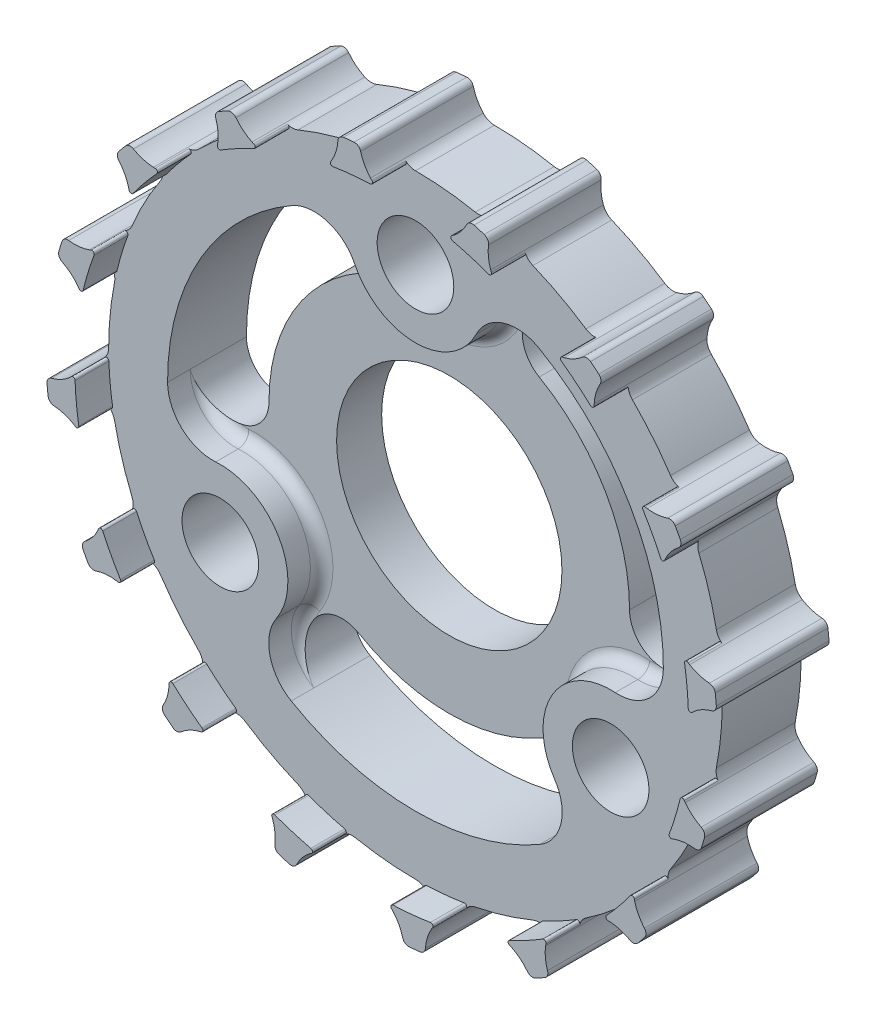
SolidWorks part; units mm, degrees
material "2018 合金"
ref_plane "正面" through (0, 0, 0) normal (0, 0, 1) x (1, 0, 0)
ref_plane "平面" through (0, 0, 0) normal (0, 1, 0) x (1, 0, 0)
ref_plane "右側面" through (0, 0, 0) normal (1, 0, 0) x (0, 0, -1)
sketch "ｽｹｯﾁ1" plane through (0, 0, 0) normal (0, 0, 1) x (1, 0, 0)
  circle A0 centre (0, 0) radius 14.9
  circle A1 centre (0, 0) radius 15.28 construction
  dimension "D1" = 29.8
  dimension "D2" = 30.56
  dimension "D3" = 0.38
extrude "ﾎﾞｽ - 押し出し1" add sketch "ｽｹｯﾁ1" along normal mid plane 7
sketch "ｽｹｯﾁ2" plane through (0, 0, 3.5) normal (0, 0, 1) x (1, 0, 0)
  line L0 (0, 0) -> (0, 16.9223) construction
  line L1 (0, 15.154) -> (0.975, 15.154) construction
  arc A0 (1.2262, 14.8495) -> (-1.2262, 14.8495) centre (0, 0) ccw
  circle A1 centre (0, 0) radius 14.9 construction
  arc A2 (0.3788, 13.7848) -> (-0.3788, 13.7848) centre (0, 0) ccw construction
  arc A3 (-0.9327, 14.6429) -> (-0.4946, 13.8345) centre (0.975, 15.154) ccw
  arc A4 (-0.4946, 13.8345) -> (-0.3788, 13.7848) centre (-0.3829, 13.9347) ccw construction
  arc A5 (-0.9327, 14.6429) -> (-1.2262, 14.8495) centre (-1.2032, 14.5704) ccw
  arc A6 (0.9327, 14.6429) -> (1.2262, 14.8495) centre (1.2032, 14.5704) cw
  arc A7 (0.4946, 13.8345) -> (0.3788, 13.7848) centre (0.3829, 13.9347) cw construction
  arc A8 (0.9327, 14.6429) -> (0.4946, 13.8345) centre (-0.975, 15.154) cw
  arc A9 (-0.4946, 13.8345) -> (0.4946, 13.8345) centre (0, 14.2786) ccw
  point P5 (0, 14.9)
  dimension "D1" = 1.11
  dimension "D4" = 1.975
  dimension "D5" = 0.28
  dimension "D6" = 0.15
  dimension "D2" = 1.95
  dimension "D3" = 0.254
extrude "ｶｯﾄ - 押し出し1" cut sketch "ｽｹｯﾁ2" against normal through all
pattern_circular "円形ﾊﾟﾀｰﾝ1" count 32 over 360 about axis through (0, 0, 3.5) along (0, 0, -1) of "ｶｯﾄ - 押し出し1"
hole_wizard "M3 すきま穴1" positions "ｽｹｯﾁ3" profile "ｽｹｯﾁ4" hole size "M3" standard "JIS" end condition through all
sketch "ｽｹｯﾁ3" plane through (0, 0, 3.5) normal (0, 0, 1) x (1, 0, 0)
  line L0 (0, 10) -> (0, 0) construction
  circle A0 centre (0, 0) radius 10
  point P0 (0, 10)
  dimension "D1" = 20
sketch "ｽｹｯﾁ4" plane through (0, 10, 3.5) normal (1, 0, 0) x (0, -1, 0)
  line L0 (0, 0) -> (0, 7)
  line L1 (0, 7) -> (1.7, 7)
  line L2 (1.7, 7) -> (1.7, 0)
  line L5 (1.7, 0) -> (0, 0)
  line L11 (0, -6.35) -> (0, 107.95) construction
  dimension "通し穴の直径" = 3.4
  dimension "通し穴の深さ" = 7
pattern_circular "円形ﾊﾟﾀｰﾝ2" count 3 over 360 about axis through (0, 0, 3.5) along (0, 0, -1) of "M3 すきま穴1"
sketch "ｽｹｯﾁ5" plane through (0, 0, 3.5) normal (0, 0, 1) x (1, 0, 0)
  line L0 (0, 10) -> (0, 11) construction
  line L1 (-3, 10) -> (-3, 11)
  line L2 (3, 10) -> (3, 11)
  line L3 (8.6603, -5) -> (9.5263, -5.5) construction
  line L4 (10.1603, -2.4019) -> (11.0263, -2.9019)
  line L5 (7.1603, -7.5981) -> (8.0263, -8.0981)
  line L6 (-8.6603, -5) -> (-9.5263, -5.5) construction
  line L7 (-7.1603, -7.5981) -> (-8.0263, -8.0981)
  line L8 (-10.1603, -2.4019) -> (-11.0263, -2.9019)
  circle A0 centre (0, 0) radius 11
  arc A1 (-3, 10) -> (3, 10) centre (0, 10) ccw
  arc A2 (3, 11) -> (-3, 11) centre (0, 11) ccw
  arc A3 (10.1603, -2.4019) -> (7.1603, -7.5981) centre (8.6603, -5) ccw
  arc A4 (8.0263, -8.0981) -> (11.0263, -2.9019) centre (9.5263, -5.5) ccw
  arc A5 (-7.1603, -7.5981) -> (-10.1603, -2.4019) centre (-8.6603, -5) ccw
  arc A6 (-11.0263, -2.9019) -> (-8.0263, -8.0981) centre (-9.5263, -5.5) ccw
  point P6 (0, 10.5)
  point P16 (9.0933, -5.25)
  point P23 (-9.0933, -5.25)
  point P28 (0, 0)
  dimension "D1" = 22
  dimension "D2" = 6
  dimension "D3" = 3
extrude "ｶｯﾄ - 押し出し2" cut sketch "ｽｹｯﾁ5" against normal offset from surface (5 mm away) 2 contours A5 L7 A0 L5 A3 L4 L2 A1 L1 L8 region at (0, 0, 3.5) up to face at (-6.9603, -5, -3.5)
fillet "ﾌｨﾚｯﾄ1" radius 2 6 edges at (-7.6652, -7.8896, 1) (7.6652, -7.8896, 1) (10.6652, -2.6934, 1) (3, 10.583, 1) (-10.6652, -2.6934, 1) (-3, 10.583, 1)
sketch "ｽｹｯﾁ6" plane through (0, 0, -1.5) normal (0, 0, 1) x (1, 0, 0)
  circle A0 centre (0, 0) radius 5
  dimension "D1" = 10
extrude "ｶｯﾄ - 押し出し3" cut sketch "ｽｹｯﾁ6" against normal through all
sketch "ｽｹｯﾁ8" plane through (0, 0, -1.5) normal (0, 0, 1) x (1, 0, 0)
  line L0 (0, 0) -> (4.7394, 8.2333) construction
  line L1 (0, 0) -> (9.5, -0.0122) construction
  arc A0 (4.7394, 8.2333) -> (9.5, -0.0122) centre (0, 0) cw construction
  arc A1 (11, -0.0141) -> (5.4878, 9.5333) centre (0, 0) ccw
  arc A2 (8, -0.0103) -> (3.9911, 6.9333) centre (0, 0) ccw
  arc A3 (8, -0.0103) -> (11, -0.0141) centre (9.5, -0.0122) ccw
  arc A4 (5.4878, 9.5333) -> (3.9911, 6.9333) centre (4.7394, 8.2333) ccw
  point P4 (8.2272, 4.75)
  dimension "D1" = 3
extrude "ｶｯﾄ - 押し出し4" cut sketch "ｽｹｯﾁ8" against normal through all
pattern_circular "円形ﾊﾟﾀｰﾝ3" count 3 over 360 about axis through (0, 0, -3.5) along (0, 0, 1) of "ｶｯﾄ - 押し出し4"
fillet "ﾌｨﾚｯﾄ2" radius 0.5 9 edges at (6.0622, -3.5, -1.5) (-6.0622, -3.5, -1.5) (0, 7, -1.5) (6.4586, -8.2389, -1.5) (10.3644, -1.4739, -1.5) (-10.3644, -1.4739, -1.5) (-6.4586, -8.2389, -1.5) (3.9058, 9.7128, -1.5) (-3.9058, 9.7128, -1.5)
chamfer "面取り1" distance 0.5 angle 45 12 edges at (0, -11, 3.5) (-6.4586, -8.2389, 3.5) (6.4586, -8.2389, 3.5) (-6.0622, -3.5, 3.5) (6.0622, -3.5, 3.5) (-10.3644, -1.4739, 3.5) (10.3644, -1.4739, 3.5) (-9.5263, 5.5, 3.5) (9.5263, 5.5, 3.5) (-3.9058, 9.7128, 3.5) (3.9058, 9.7128, 3.5) (0, 7, 3.5)
sketch "ｽｹｯﾁ9" plane through (0, 0, 3.5) normal (0, 0, 1) x (1, 0, 0)
  circle A0 centre (0, 0) radius 13.6139
  arc A192 (4.7419, 13.8852) -> (4.5498, 14.1884) centre (4.4643, 13.9217) ccw
  arc A193 (4.5498, 14.1884) -> (4.0996, 14.3249) centre (0, 0) ccw
  arc A194 (4.0996, 14.3249) -> (3.7715, 14.1795) centre (4.0226, 14.0557) ccw
  arc A195 (3.184, 13.4722) -> (3.7715, 14.1795) centre (2.0001, 15.053) ccw
  arc A196 (2.2139, 13.6652) -> (3.184, 13.4722) centre (2.7856, 14.0042) ccw
  arc A197 (1.9419, 14.5435) -> (2.2139, 13.6652) centre (3.9127, 14.6726) ccw
  arc A198 (1.9419, 14.5435) -> (1.6943, 14.8034) centre (1.6625, 14.5252) ccw
  arc A199 (1.6943, 14.8034) -> (1.2262, 14.8495) centre (0, 0) ccw
  arc A200 (1.2262, 14.8495) -> (0.9327, 14.6429) centre (1.2032, 14.5704) ccw
  arc A201 (0.4946, 13.8345) -> (0.9327, 14.6429) centre (-0.975, 15.154) ccw
  arc A202 (-0.4946, 13.8345) -> (0.4946, 13.8345) centre (0, 14.2786) ccw
  arc A203 (-0.9327, 14.6429) -> (-0.4946, 13.8345) centre (0.975, 15.154) ccw
  arc A204 (-0.9327, 14.6429) -> (-1.2262, 14.8495) centre (-1.2032, 14.5704) ccw
  arc A205 (-1.2262, 14.8495) -> (-1.6943, 14.8034) centre (0, 0) ccw
  arc A206 (-1.6943, 14.8034) -> (-1.9419, 14.5435) centre (-1.6625, 14.5252) ccw
  arc A207 (-2.2139, 13.6652) -> (-1.9419, 14.5435) centre (-3.9127, 14.6726) ccw
  arc A208 (-3.184, 13.4722) -> (-2.2139, 13.6652) centre (-2.7856, 14.0042) ccw
  arc A209 (-3.7715, 14.1795) -> (-3.184, 13.4722) centre (-2.0001, 15.053) ccw
  arc A210 (-3.7715, 14.1795) -> (-4.0996, 14.3249) centre (-4.0226, 14.0557) ccw
  arc A211 (-4.0996, 14.3249) -> (-4.5498, 14.1884) centre (0, 0) ccw
  arc A212 (-4.5498, 14.1884) -> (-4.7419, 13.8852) centre (-4.4643, 13.9217) ccw
  arc A213 (-4.8373, 12.9707) -> (-4.7419, 13.8852) centre (-6.7, 13.6274) ccw
  arc A214 (-5.7512, 12.5922) -> (-4.8373, 12.9707) centre (-5.4642, 13.1917) ccw
  arc A215 (-6.4653, 13.1713) -> (-5.7512, 12.5922) centre (-4.8984, 14.3736) ccw
  arc A216 (-6.4653, 13.1713) -> (-6.8155, 13.2499) centre (-6.6874, 13.0009) ccw
  arc A217 (-6.8155, 13.2499) -> (-7.2304, 13.0281) centre (0, 0) ccw
  arc A218 (-7.2304, 13.0281) -> (-7.3596, 12.6933) centre (-7.0945, 12.7833) ccw
  arc A219 (-7.2748, 11.7778) -> (-7.3596, 12.6933) centre (-9.2298, 12.0584) ccw
  arc A220 (-8.0973, 11.2282) -> (-7.2748, 11.7778) centre (-7.9328, 11.8722) ccw
  arc A221 (-8.9107, 11.6569) -> (-8.0973, 11.2282) centre (-7.6084, 13.1418) ccw
  arc A222 (-8.9107, 11.6569) -> (-9.2695, 11.6656) centre (-9.0953, 11.4464) ccw
  arc A223 (-9.2695, 11.6656) -> (-9.6331, 11.3672) centre (0, 0) ccw
  arc A224 (-9.6331, 11.3672) -> (-9.6945, 11.0136) centre (-9.4521, 11.1536) ccw
  arc A225 (-9.4328, 10.1322) -> (-9.6945, 11.0136) centre (-11.4049, 10.0261) ccw
  arc A226 (-10.1322, 9.4328) -> (-9.4328, 10.1322) centre (-10.0965, 10.0965) ccw
  arc A227 (-11.0136, 9.6945) -> (-10.1322, 9.4328) centre (-10.0261, 11.4049) ccw
  arc A228 (-11.0136, 9.6945) -> (-11.3672, 9.6331) centre (-11.1536, 9.4521) ccw
  arc A229 (-11.3672, 9.6331) -> (-11.6656, 9.2695) centre (0, 0) ccw
  arc A230 (-11.6656, 9.2695) -> (-11.6569, 8.9107) centre (-11.4464, 9.0953) ccw
  arc A231 (-11.2282, 8.0973) -> (-11.6569, 8.9107) centre (-13.1418, 7.6084) ccw
  arc A232 (-11.7778, 7.2748) -> (-11.2282, 8.0973) centre (-11.8722, 7.9328) ccw
  arc A233 (-12.6933, 7.3596) -> (-11.7778, 7.2748) centre (-12.0584, 9.2298) ccw
  arc A234 (-12.6933, 7.3596) -> (-13.0281, 7.2304) centre (-12.7833, 7.0945) ccw
  arc A235 (-13.0281, 7.2304) -> (-13.2499, 6.8155) centre (0, 0) ccw
  arc A236 (-13.2499, 6.8155) -> (-13.1713, 6.4653) centre (-13.0009, 6.6874) ccw
  arc A237 (-12.5922, 5.7512) -> (-13.1713, 6.4653) centre (-14.3736, 4.8984) ccw
  arc A238 (-12.9707, 4.8373) -> (-12.5922, 5.7512) centre (-13.1917, 5.4642) ccw
  arc A239 (-13.8852, 4.7419) -> (-12.9707, 4.8373) centre (-13.6274, 6.7) ccw
  arc A240 (-13.8852, 4.7419) -> (-14.1884, 4.5498) centre (-13.9217, 4.4643) ccw
  arc A241 (-14.1884, 4.5498) -> (-14.3249, 4.0996) centre (0, 0) ccw
  arc A242 (-14.3249, 4.0996) -> (-14.1795, 3.7715) centre (-14.0557, 4.0226) ccw
  arc A243 (-13.4722, 3.184) -> (-14.1795, 3.7715) centre (-15.053, 2.0001) ccw
  arc A244 (-13.6652, 2.2139) -> (-13.4722, 3.184) centre (-14.0042, 2.7856) ccw
  arc A245 (-14.5435, 1.9419) -> (-13.6652, 2.2139) centre (-14.6726, 3.9127) ccw
  arc A246 (-14.5435, 1.9419) -> (-14.8034, 1.6943) centre (-14.5252, 1.6625) ccw
  arc A247 (-14.8034, 1.6943) -> (-14.8495, 1.2262) centre (0, 0) ccw
  arc A248 (-14.8495, 1.2262) -> (-14.6429, 0.9327) centre (-14.5704, 1.2032) ccw
  arc A249 (-13.8345, 0.4946) -> (-14.6429, 0.9327) centre (-15.154, -0.975) ccw
  arc A250 (-13.8345, -0.4946) -> (-13.8345, 0.4946) centre (-14.2786, 0) ccw
  arc A251 (-14.6429, -0.9327) -> (-13.8345, -0.4946) centre (-15.154, 0.975) ccw
  arc A252 (-14.6429, -0.9327) -> (-14.8495, -1.2262) centre (-14.5704, -1.2032) ccw
  arc A253 (-14.8495, -1.2262) -> (-14.8034, -1.6943) centre (0, 0) ccw
  arc A254 (-14.8034, -1.6943) -> (-14.5435, -1.9419) centre (-14.5252, -1.6625) ccw
  arc A255 (-13.6652, -2.2139) -> (-14.5435, -1.9419) centre (-14.6726, -3.9127) ccw
  arc A256 (-13.4722, -3.184) -> (-13.6652, -2.2139) centre (-14.0042, -2.7856) ccw
  arc A257 (-14.1795, -3.7715) -> (-13.4722, -3.184) centre (-15.053, -2.0001) ccw
  arc A258 (-14.1795, -3.7715) -> (-14.3249, -4.0996) centre (-14.0557, -4.0226) ccw
  arc A259 (-14.3249, -4.0996) -> (-14.1884, -4.5498) centre (0, 0) ccw
  arc A260 (-14.1884, -4.5498) -> (-13.8852, -4.7419) centre (-13.9217, -4.4643) ccw
  arc A261 (-12.9707, -4.8373) -> (-13.8852, -4.7419) centre (-13.6274, -6.7) ccw
  arc A262 (-12.5922, -5.7512) -> (-12.9707, -4.8373) centre (-13.1917, -5.4642) ccw
  arc A263 (-13.1713, -6.4653) -> (-12.5922, -5.7512) centre (-14.3736, -4.8984) ccw
  arc A264 (-13.1713, -6.4653) -> (-13.2499, -6.8155) centre (-13.0009, -6.6874) ccw
  arc A265 (-13.2499, -6.8155) -> (-13.0281, -7.2304) centre (0, 0) ccw
  arc A266 (-13.0281, -7.2304) -> (-12.6933, -7.3596) centre (-12.7833, -7.0945) ccw
  arc A267 (-11.7778, -7.2748) -> (-12.6933, -7.3596) centre (-12.0584, -9.2298) ccw
  arc A268 (-11.2282, -8.0973) -> (-11.7778, -7.2748) centre (-11.8722, -7.9328) ccw
  arc A269 (-11.6569, -8.9107) -> (-11.2282, -8.0973) centre (-13.1418, -7.6084) ccw
  arc A270 (-11.6569, -8.9107) -> (-11.6656, -9.2695) centre (-11.4464, -9.0953) ccw
  arc A271 (-11.6656, -9.2695) -> (-11.3672, -9.6331) centre (0, 0) ccw
  arc A272 (-11.3672, -9.6331) -> (-11.0136, -9.6945) centre (-11.1536, -9.4521) ccw
  arc A273 (-10.1322, -9.4328) -> (-11.0136, -9.6945) centre (-10.0261, -11.4049) ccw
  arc A274 (-9.4328, -10.1322) -> (-10.1322, -9.4328) centre (-10.0965, -10.0965) ccw
  arc A275 (-9.6945, -11.0136) -> (-9.4328, -10.1322) centre (-11.4049, -10.0261) ccw
  arc A276 (-9.6945, -11.0136) -> (-9.6331, -11.3672) centre (-9.4521, -11.1536) ccw
  arc A277 (-9.6331, -11.3672) -> (-9.2695, -11.6656) centre (0, 0) ccw
  arc A278 (-9.2695, -11.6656) -> (-8.9107, -11.6569) centre (-9.0953, -11.4464) ccw
  arc A279 (-8.0973, -11.2282) -> (-8.9107, -11.6569) centre (-7.6084, -13.1418) ccw
  arc A280 (-7.2748, -11.7778) -> (-8.0973, -11.2282) centre (-7.9328, -11.8722) ccw
  arc A281 (-7.3596, -12.6933) -> (-7.2748, -11.7778) centre (-9.2298, -12.0584) ccw
  arc A282 (-7.3596, -12.6933) -> (-7.2304, -13.0281) centre (-7.0945, -12.7833) ccw
  arc A283 (-7.2304, -13.0281) -> (-6.8155, -13.2499) centre (0, 0) ccw
  arc A284 (-6.8155, -13.2499) -> (-6.4653, -13.1713) centre (-6.6874, -13.0009) ccw
  arc A285 (-5.7512, -12.5922) -> (-6.4653, -13.1713) centre (-4.8984, -14.3736) ccw
  arc A286 (-4.8373, -12.9707) -> (-5.7512, -12.5922) centre (-5.4642, -13.1917) ccw
  arc A287 (-4.7419, -13.8852) -> (-4.8373, -12.9707) centre (-6.7, -13.6274) ccw
  arc A288 (-4.7419, -13.8852) -> (-4.5498, -14.1884) centre (-4.4643, -13.9217) ccw
  arc A289 (-4.5498, -14.1884) -> (-4.0996, -14.3249) centre (0, 0) ccw
  arc A290 (-4.0996, -14.3249) -> (-3.7715, -14.1795) centre (-4.0226, -14.0557) ccw
  arc A291 (-3.184, -13.4722) -> (-3.7715, -14.1795) centre (-2.0001, -15.053) ccw
  arc A292 (-2.2139, -13.6652) -> (-3.184, -13.4722) centre (-2.7856, -14.0042) ccw
  arc A293 (-1.9419, -14.5435) -> (-2.2139, -13.6652) centre (-3.9127, -14.6726) ccw
  arc A294 (-1.9419, -14.5435) -> (-1.6943, -14.8034) centre (-1.6625, -14.5252) ccw
  arc A295 (-1.6943, -14.8034) -> (-1.2262, -14.8495) centre (0, 0) ccw
  arc A296 (-1.2262, -14.8495) -> (-0.9327, -14.6429) centre (-1.2032, -14.5704) ccw
  arc A297 (-0.4946, -13.8345) -> (-0.9327, -14.6429) centre (0.975, -15.154) ccw
  arc A298 (0.4946, -13.8345) -> (-0.4946, -13.8345) centre (0, -14.2786) ccw
  arc A299 (0.9327, -14.6429) -> (0.4946, -13.8345) centre (-0.975, -15.154) ccw
  arc A300 (0.9327, -14.6429) -> (1.2262, -14.8495) centre (1.2032, -14.5704) ccw
  arc A301 (1.2262, -14.8495) -> (1.6943, -14.8034) centre (0, 0) ccw
  arc A302 (1.6943, -14.8034) -> (1.9419, -14.5435) centre (1.6625, -14.5252) ccw
  arc A303 (2.2139, -13.6652) -> (1.9419, -14.5435) centre (3.9127, -14.6726) ccw
  arc A304 (3.184, -13.4722) -> (2.2139, -13.6652) centre (2.7856, -14.0042) ccw
  arc A305 (3.7715, -14.1795) -> (3.184, -13.4722) centre (2.0001, -15.053) ccw
  arc A306 (3.7715, -14.1795) -> (4.0996, -14.3249) centre (4.0226, -14.0557) ccw
  arc A307 (4.0996, -14.3249) -> (4.5498, -14.1884) centre (0, 0) ccw
  arc A308 (4.5498, -14.1884) -> (4.7419, -13.8852) centre (4.4643, -13.9217) ccw
  arc A309 (4.8373, -12.9707) -> (4.7419, -13.8852) centre (6.7, -13.6274) ccw
  arc A310 (5.7512, -12.5922) -> (4.8373, -12.9707) centre (5.4642, -13.1917) ccw
  arc A311 (6.4653, -13.1713) -> (5.7512, -12.5922) centre (4.8984, -14.3736) ccw
  arc A312 (6.4653, -13.1713) -> (6.8155, -13.2499) centre (6.6874, -13.0009) ccw
  arc A313 (6.8155, -13.2499) -> (7.2304, -13.0281) centre (0, 0) ccw
  arc A314 (7.2304, -13.0281) -> (7.3596, -12.6933) centre (7.0945, -12.7833) ccw
  arc A315 (7.2748, -11.7778) -> (7.3596, -12.6933) centre (9.2298, -12.0584) ccw
  arc A316 (8.0973, -11.2282) -> (7.2748, -11.7778) centre (7.9328, -11.8722) ccw
  arc A317 (8.9107, -11.6569) -> (8.0973, -11.2282) centre (7.6084, -13.1418) ccw
  arc A318 (8.9107, -11.6569) -> (9.2695, -11.6656) centre (9.0953, -11.4464) ccw
  arc A319 (9.2695, -11.6656) -> (9.6331, -11.3672) centre (0, 0) ccw
  arc A320 (9.6331, -11.3672) -> (9.6945, -11.0136) centre (9.4521, -11.1536) ccw
  arc A321 (9.4328, -10.1322) -> (9.6945, -11.0136) centre (11.4049, -10.0261) ccw
  arc A322 (10.1322, -9.4328) -> (9.4328, -10.1322) centre (10.0965, -10.0965) ccw
  arc A323 (11.0136, -9.6945) -> (10.1322, -9.4328) centre (10.0261, -11.4049) ccw
  arc A324 (11.0136, -9.6945) -> (11.3672, -9.6331) centre (11.1536, -9.4521) ccw
  arc A325 (11.3672, -9.6331) -> (11.6656, -9.2695) centre (0, 0) ccw
  arc A326 (11.6656, -9.2695) -> (11.6569, -8.9107) centre (11.4464, -9.0953) ccw
  arc A327 (11.2282, -8.0973) -> (11.6569, -8.9107) centre (13.1418, -7.6084) ccw
  arc A328 (11.7778, -7.2748) -> (11.2282, -8.0973) centre (11.8722, -7.9328) ccw
  arc A329 (12.6933, -7.3596) -> (11.7778, -7.2748) centre (12.0584, -9.2298) ccw
  arc A330 (12.6933, -7.3596) -> (13.0281, -7.2304) centre (12.7833, -7.0945) ccw
  arc A331 (13.0281, -7.2304) -> (13.2499, -6.8155) centre (0, 0) ccw
  arc A332 (13.2499, -6.8155) -> (13.1713, -6.4653) centre (13.0009, -6.6874) ccw
  arc A333 (12.5922, -5.7512) -> (13.1713, -6.4653) centre (14.3736, -4.8984) ccw
  arc A334 (12.9707, -4.8373) -> (12.5922, -5.7512) centre (13.1917, -5.4642) ccw
  arc A335 (13.8852, -4.7419) -> (12.9707, -4.8373) centre (13.6274, -6.7) ccw
  arc A336 (13.8852, -4.7419) -> (14.1884, -4.5498) centre (13.9217, -4.4643) ccw
  arc A337 (14.1884, -4.5498) -> (14.3249, -4.0996) centre (0, 0) ccw
  arc A338 (14.3249, -4.0996) -> (14.1795, -3.7715) centre (14.0557, -4.0226) ccw
  arc A339 (13.4722, -3.184) -> (14.1795, -3.7715) centre (15.053, -2.0001) ccw
  arc A340 (13.6652, -2.2139) -> (13.4722, -3.184) centre (14.0042, -2.7856) ccw
  arc A341 (14.5435, -1.9419) -> (13.6652, -2.2139) centre (14.6726, -3.9127) ccw
  arc A342 (14.5435, -1.9419) -> (14.8034, -1.6943) centre (14.5252, -1.6625) ccw
  arc A343 (14.8034, -1.6943) -> (14.8495, -1.2262) centre (0, 0) ccw
  arc A344 (14.8495, -1.2262) -> (14.6429, -0.9327) centre (14.5704, -1.2032) ccw
  arc A345 (13.8345, -0.4946) -> (14.6429, -0.9327) centre (15.154, 0.975) ccw
  arc A346 (13.8345, 0.4946) -> (13.8345, -0.4946) centre (14.2786, 0) ccw
  arc A347 (14.6429, 0.9327) -> (13.8345, 0.4946) centre (15.154, -0.975) ccw
  arc A348 (14.6429, 0.9327) -> (14.8495, 1.2262) centre (14.5704, 1.2032) ccw
  arc A349 (14.8495, 1.2262) -> (14.8034, 1.6943) centre (0, 0) ccw
  arc A350 (14.8034, 1.6943) -> (14.5435, 1.9419) centre (14.5252, 1.6625) ccw
  arc A351 (13.6652, 2.2139) -> (14.5435, 1.9419) centre (14.6726, 3.9127) ccw
  arc A352 (13.4722, 3.184) -> (13.6652, 2.2139) centre (14.0042, 2.7856) ccw
  arc A353 (14.1795, 3.7715) -> (13.4722, 3.184) centre (15.053, 2.0001) ccw
  arc A354 (14.1795, 3.7715) -> (14.3249, 4.0996) centre (14.0557, 4.0226) ccw
  arc A355 (14.3249, 4.0996) -> (14.1884, 4.5498) centre (0, 0) ccw
  arc A356 (14.1884, 4.5498) -> (13.8852, 4.7419) centre (13.9217, 4.4643) ccw
  arc A357 (12.9707, 4.8373) -> (13.8852, 4.7419) centre (13.6274, 6.7) ccw
  arc A358 (12.5922, 5.7512) -> (12.9707, 4.8373) centre (13.1917, 5.4642) ccw
  arc A359 (13.1713, 6.4653) -> (12.5922, 5.7512) centre (14.3736, 4.8984) ccw
  arc A360 (13.1713, 6.4653) -> (13.2499, 6.8155) centre (13.0009, 6.6874) ccw
  arc A361 (13.2499, 6.8155) -> (13.0281, 7.2304) centre (0, 0) ccw
  arc A362 (13.0281, 7.2304) -> (12.6933, 7.3596) centre (12.7833, 7.0945) ccw
  arc A363 (11.7778, 7.2748) -> (12.6933, 7.3596) centre (12.0584, 9.2298) ccw
  arc A364 (11.2282, 8.0973) -> (11.7778, 7.2748) centre (11.8722, 7.9328) ccw
  arc A365 (11.6569, 8.9107) -> (11.2282, 8.0973) centre (13.1418, 7.6084) ccw
  arc A366 (11.6569, 8.9107) -> (11.6656, 9.2695) centre (11.4464, 9.0953) ccw
  arc A367 (11.6656, 9.2695) -> (11.3672, 9.6331) centre (0, 0) ccw
  arc A368 (11.3672, 9.6331) -> (11.0136, 9.6945) centre (11.1536, 9.4521) ccw
  arc A369 (10.1322, 9.4328) -> (11.0136, 9.6945) centre (10.0261, 11.4049) ccw
  arc A370 (9.4328, 10.1322) -> (10.1322, 9.4328) centre (10.0965, 10.0965) ccw
  arc A371 (9.6945, 11.0136) -> (9.4328, 10.1322) centre (11.4049, 10.0261) ccw
  arc A372 (9.6945, 11.0136) -> (9.6331, 11.3672) centre (9.4521, 11.1536) ccw
  arc A373 (9.6331, 11.3672) -> (9.2695, 11.6656) centre (0, 0) ccw
  arc A374 (9.2695, 11.6656) -> (8.9107, 11.6569) centre (9.0953, 11.4464) ccw
  arc A375 (8.0973, 11.2282) -> (8.9107, 11.6569) centre (7.6084, 13.1418) ccw
  arc A376 (7.2748, 11.7778) -> (8.0973, 11.2282) centre (7.9328, 11.8722) ccw
  arc A377 (7.3596, 12.6933) -> (7.2748, 11.7778) centre (9.2298, 12.0584) ccw
  arc A378 (7.3596, 12.6933) -> (7.2304, 13.0281) centre (7.0945, 12.7833) ccw
  arc A379 (7.2304, 13.0281) -> (6.8155, 13.2499) centre (0, 0) ccw
  arc A380 (6.8155, 13.2499) -> (6.4653, 13.1713) centre (6.6874, 13.0009) ccw
  arc A381 (5.7512, 12.5922) -> (6.4653, 13.1713) centre (4.8984, 14.3736) ccw
  arc A382 (4.8373, 12.9707) -> (5.7512, 12.5922) centre (5.4642, 13.1917) ccw
  arc A383 (4.7419, 13.8852) -> (4.8373, 12.9707) centre (6.7, 13.6274) ccw
  arc A384 (4.7419, 13.8852) -> (4.5498, 14.1884) centre (4.4643, 13.9217) ccw
  arc A385 (4.5498, 14.1884) -> (4.0996, 14.3249) centre (0, 0) ccw
  arc A386 (4.0996, 14.3249) -> (3.7715, 14.1795) centre (4.0226, 14.0557) ccw
  arc A387 (3.184, 13.4722) -> (3.7715, 14.1795) centre (2.0001, 15.053) ccw
  arc A388 (2.2139, 13.6652) -> (3.184, 13.4722) centre (2.7856, 14.0042) ccw
  arc A389 (1.9419, 14.5435) -> (2.2139, 13.6652) centre (3.9127, 14.6726) ccw
  arc A390 (1.9419, 14.5435) -> (1.6943, 14.8034) centre (1.6625, 14.5252) ccw
  arc A391 (1.6943, 14.8034) -> (1.2262, 14.8495) centre (0, 0) ccw
  arc A392 (1.2262, 14.8495) -> (0.9327, 14.6429) centre (1.2032, 14.5704) ccw
  arc A393 (0.4946, 13.8345) -> (0.9327, 14.6429) centre (-0.975, 15.154) ccw
  arc A394 (-0.4946, 13.8345) -> (0.4946, 13.8345) centre (0, 14.2786) ccw
  arc A395 (-0.9327, 14.6429) -> (-0.4946, 13.8345) centre (0.975, 15.154) ccw
  arc A396 (-0.9327, 14.6429) -> (-1.2262, 14.8495) centre (-1.2032, 14.5704) ccw
  arc A397 (-1.2262, 14.8495) -> (-1.6943, 14.8034) centre (0, 0) ccw
  arc A398 (-1.6943, 14.8034) -> (-1.9419, 14.5435) centre (-1.6625, 14.5252) ccw
  arc A399 (-2.2139, 13.6652) -> (-1.9419, 14.5435) centre (-3.9127, 14.6726) ccw
  arc A400 (-3.184, 13.4722) -> (-2.2139, 13.6652) centre (-2.7856, 14.0042) ccw
  arc A401 (-3.7715, 14.1795) -> (-3.184, 13.4722) centre (-2.0001, 15.053) ccw
  arc A402 (-3.7715, 14.1795) -> (-4.0996, 14.3249) centre (-4.0226, 14.0557) ccw
  arc A403 (-4.0996, 14.3249) -> (-4.5498, 14.1884) centre (0, 0) ccw
  arc A404 (-4.5498, 14.1884) -> (-4.7419, 13.8852) centre (-4.4643, 13.9217) ccw
  arc A405 (-4.8373, 12.9707) -> (-4.7419, 13.8852) centre (-6.7, 13.6274) ccw
  arc A406 (-5.7512, 12.5922) -> (-4.8373, 12.9707) centre (-5.4642, 13.1917) ccw
  arc A407 (-6.4653, 13.1713) -> (-5.7512, 12.5922) centre (-4.8984, 14.3736) ccw
  arc A408 (-6.4653, 13.1713) -> (-6.8155, 13.2499) centre (-6.6874, 13.0009) ccw
  arc A409 (-6.8155, 13.2499) -> (-7.2304, 13.0281) centre (0, 0) ccw
  arc A410 (-7.2304, 13.0281) -> (-7.3596, 12.6933) centre (-7.0945, 12.7833) ccw
  arc A411 (-7.2748, 11.7778) -> (-7.3596, 12.6933) centre (-9.2298, 12.0584) ccw
  arc A412 (-8.0973, 11.2282) -> (-7.2748, 11.7778) centre (-7.9328, 11.8722) ccw
  arc A413 (-8.9107, 11.6569) -> (-8.0973, 11.2282) centre (-7.6084, 13.1418) ccw
  arc A414 (-8.9107, 11.6569) -> (-9.2695, 11.6656) centre (-9.0953, 11.4464) ccw
  arc A415 (-9.2695, 11.6656) -> (-9.6331, 11.3672) centre (0, 0) ccw
  arc A416 (-9.6331, 11.3672) -> (-9.6945, 11.0136) centre (-9.4521, 11.1536) ccw
  arc A417 (-9.4328, 10.1322) -> (-9.6945, 11.0136) centre (-11.4049, 10.0261) ccw
  arc A418 (-10.1322, 9.4328) -> (-9.4328, 10.1322) centre (-10.0965, 10.0965) ccw
  arc A419 (-11.0136, 9.6945) -> (-10.1322, 9.4328) centre (-10.0261, 11.4049) ccw
  arc A420 (-11.0136, 9.6945) -> (-11.3672, 9.6331) centre (-11.1536, 9.4521) ccw
  arc A421 (-11.3672, 9.6331) -> (-11.6656, 9.2695) centre (0, 0) ccw
  arc A422 (-11.6656, 9.2695) -> (-11.6569, 8.9107) centre (-11.4464, 9.0953) ccw
  arc A423 (-11.2282, 8.0973) -> (-11.6569, 8.9107) centre (-13.1418, 7.6084) ccw
  arc A424 (-11.7778, 7.2748) -> (-11.2282, 8.0973) centre (-11.8722, 7.9328) ccw
  arc A425 (-12.6933, 7.3596) -> (-11.7778, 7.2748) centre (-12.0584, 9.2298) ccw
  arc A426 (-12.6933, 7.3596) -> (-13.0281, 7.2304) centre (-12.7833, 7.0945) ccw
  arc A427 (-13.0281, 7.2304) -> (-13.2499, 6.8155) centre (0, 0) ccw
  arc A428 (-13.2499, 6.8155) -> (-13.1713, 6.4653) centre (-13.0009, 6.6874) ccw
  arc A429 (-12.5922, 5.7512) -> (-13.1713, 6.4653) centre (-14.3736, 4.8984) ccw
  arc A430 (-12.9707, 4.8373) -> (-12.5922, 5.7512) centre (-13.1917, 5.4642) ccw
  arc A431 (-13.8852, 4.7419) -> (-12.9707, 4.8373) centre (-13.6274, 6.7) ccw
  arc A432 (-13.8852, 4.7419) -> (-14.1884, 4.5498) centre (-13.9217, 4.4643) ccw
  arc A433 (-14.1884, 4.5498) -> (-14.3249, 4.0996) centre (0, 0) ccw
  arc A434 (-14.3249, 4.0996) -> (-14.1795, 3.7715) centre (-14.0557, 4.0226) ccw
  arc A435 (-13.4722, 3.184) -> (-14.1795, 3.7715) centre (-15.053, 2.0001) ccw
  arc A436 (-13.6652, 2.2139) -> (-13.4722, 3.184) centre (-14.0042, 2.7856) ccw
  arc A437 (-14.5435, 1.9419) -> (-13.6652, 2.2139) centre (-14.6726, 3.9127) ccw
  arc A438 (-14.5435, 1.9419) -> (-14.8034, 1.6943) centre (-14.5252, 1.6625) ccw
  arc A439 (-14.8034, 1.6943) -> (-14.8495, 1.2262) centre (0, 0) ccw
  arc A440 (-14.8495, 1.2262) -> (-14.6429, 0.9327) centre (-14.5704, 1.2032) ccw
  arc A441 (-13.8345, 0.4946) -> (-14.6429, 0.9327) centre (-15.154, -0.975) ccw
  arc A442 (-13.8345, -0.4946) -> (-13.8345, 0.4946) centre (-14.2786, 0) ccw
  arc A443 (-14.6429, -0.9327) -> (-13.8345, -0.4946) centre (-15.154, 0.975) ccw
  arc A444 (-14.6429, -0.9327) -> (-14.8495, -1.2262) centre (-14.5704, -1.2032) ccw
  arc A445 (-14.8495, -1.2262) -> (-14.8034, -1.6943) centre (0, 0) ccw
  arc A446 (-14.8034, -1.6943) -> (-14.5435, -1.9419) centre (-14.5252, -1.6625) ccw
  arc A447 (-13.6652, -2.2139) -> (-14.5435, -1.9419) centre (-14.6726, -3.9127) ccw
  arc A448 (-13.4722, -3.184) -> (-13.6652, -2.2139) centre (-14.0042, -2.7856) ccw
  arc A449 (-14.1795, -3.7715) -> (-13.4722, -3.184) centre (-15.053, -2.0001) ccw
  arc A450 (-14.1795, -3.7715) -> (-14.3249, -4.0996) centre (-14.0557, -4.0226) ccw
  arc A451 (-14.3249, -4.0996) -> (-14.1884, -4.5498) centre (0, 0) ccw
  arc A452 (-14.1884, -4.5498) -> (-13.8852, -4.7419) centre (-13.9217, -4.4643) ccw
  arc A453 (-12.9707, -4.8373) -> (-13.8852, -4.7419) centre (-13.6274, -6.7) ccw
  arc A454 (-12.5922, -5.7512) -> (-12.9707, -4.8373) centre (-13.1917, -5.4642) ccw
  arc A455 (-13.1713, -6.4653) -> (-12.5922, -5.7512) centre (-14.3736, -4.8984) ccw
  arc A456 (-13.1713, -6.4653) -> (-13.2499, -6.8155) centre (-13.0009, -6.6874) ccw
  arc A457 (-13.2499, -6.8155) -> (-13.0281, -7.2304) centre (0, 0) ccw
  arc A458 (-13.0281, -7.2304) -> (-12.6933, -7.3596) centre (-12.7833, -7.0945) ccw
  arc A459 (-11.7778, -7.2748) -> (-12.6933, -7.3596) centre (-12.0584, -9.2298) ccw
  arc A460 (-11.2282, -8.0973) -> (-11.7778, -7.2748) centre (-11.8722, -7.9328) ccw
  arc A461 (-11.6569, -8.9107) -> (-11.2282, -8.0973) centre (-13.1418, -7.6084) ccw
  arc A462 (-11.6569, -8.9107) -> (-11.6656, -9.2695) centre (-11.4464, -9.0953) ccw
  arc A463 (-11.6656, -9.2695) -> (-11.3672, -9.6331) centre (0, 0) ccw
  arc A464 (-11.3672, -9.6331) -> (-11.0136, -9.6945) centre (-11.1536, -9.4521) ccw
  arc A465 (-10.1322, -9.4328) -> (-11.0136, -9.6945) centre (-10.0261, -11.4049) ccw
  arc A466 (-9.4328, -10.1322) -> (-10.1322, -9.4328) centre (-10.0965, -10.0965) ccw
  arc A467 (-9.6945, -11.0136) -> (-9.4328, -10.1322) centre (-11.4049, -10.0261) ccw
  arc A468 (-9.6945, -11.0136) -> (-9.6331, -11.3672) centre (-9.4521, -11.1536) ccw
  arc A469 (-9.6331, -11.3672) -> (-9.2695, -11.6656) centre (0, 0) ccw
  arc A470 (-9.2695, -11.6656) -> (-8.9107, -11.6569) centre (-9.0953, -11.4464) ccw
  arc A471 (-8.0973, -11.2282) -> (-8.9107, -11.6569) centre (-7.6084, -13.1418) ccw
  arc A472 (-7.2748, -11.7778) -> (-8.0973, -11.2282) centre (-7.9328, -11.8722) ccw
  arc A473 (-7.3596, -12.6933) -> (-7.2748, -11.7778) centre (-9.2298, -12.0584) ccw
  arc A474 (-7.3596, -12.6933) -> (-7.2304, -13.0281) centre (-7.0945, -12.7833) ccw
  arc A475 (-7.2304, -13.0281) -> (-6.8155, -13.2499) centre (0, 0) ccw
  arc A476 (-6.8155, -13.2499) -> (-6.4653, -13.1713) centre (-6.6874, -13.0009) ccw
  arc A477 (-5.7512, -12.5922) -> (-6.4653, -13.1713) centre (-4.8984, -14.3736) ccw
  arc A478 (-4.8373, -12.9707) -> (-5.7512, -12.5922) centre (-5.4642, -13.1917) ccw
  arc A479 (-4.7419, -13.8852) -> (-4.8373, -12.9707) centre (-6.7, -13.6274) ccw
  arc A480 (-4.7419, -13.8852) -> (-4.5498, -14.1884) centre (-4.4643, -13.9217) ccw
  arc A481 (-4.5498, -14.1884) -> (-4.0996, -14.3249) centre (0, 0) ccw
  arc A482 (-4.0996, -14.3249) -> (-3.7715, -14.1795) centre (-4.0226, -14.0557) ccw
  arc A483 (-3.184, -13.4722) -> (-3.7715, -14.1795) centre (-2.0001, -15.053) ccw
  arc A484 (-2.2139, -13.6652) -> (-3.184, -13.4722) centre (-2.7856, -14.0042) ccw
  arc A485 (-1.9419, -14.5435) -> (-2.2139, -13.6652) centre (-3.9127, -14.6726) ccw
  arc A486 (-1.9419, -14.5435) -> (-1.6943, -14.8034) centre (-1.6625, -14.5252) ccw
  arc A487 (-1.6943, -14.8034) -> (-1.2262, -14.8495) centre (0, 0) ccw
  arc A488 (-1.2262, -14.8495) -> (-0.9327, -14.6429) centre (-1.2032, -14.5704) ccw
  arc A489 (-0.4946, -13.8345) -> (-0.9327, -14.6429) centre (0.975, -15.154) ccw
  arc A490 (0.4946, -13.8345) -> (-0.4946, -13.8345) centre (0, -14.2786) ccw
  arc A491 (0.9327, -14.6429) -> (0.4946, -13.8345) centre (-0.975, -15.154) ccw
  arc A492 (0.9327, -14.6429) -> (1.2262, -14.8495) centre (1.2032, -14.5704) ccw
  arc A493 (1.2262, -14.8495) -> (1.6943, -14.8034) centre (0, 0) ccw
  arc A494 (1.6943, -14.8034) -> (1.9419, -14.5435) centre (1.6625, -14.5252) ccw
  arc A495 (2.2139, -13.6652) -> (1.9419, -14.5435) centre (3.9127, -14.6726) ccw
  arc A496 (3.184, -13.4722) -> (2.2139, -13.6652) centre (2.7856, -14.0042) ccw
  arc A497 (3.7715, -14.1795) -> (3.184, -13.4722) centre (2.0001, -15.053) ccw
  arc A498 (3.7715, -14.1795) -> (4.0996, -14.3249) centre (4.0226, -14.0557) ccw
  arc A499 (4.0996, -14.3249) -> (4.5498, -14.1884) centre (0, 0) ccw
  arc A500 (4.5498, -14.1884) -> (4.7419, -13.8852) centre (4.4643, -13.9217) ccw
  arc A501 (4.8373, -12.9707) -> (4.7419, -13.8852) centre (6.7, -13.6274) ccw
  arc A502 (5.7512, -12.5922) -> (4.8373, -12.9707) centre (5.4642, -13.1917) ccw
  arc A503 (6.4653, -13.1713) -> (5.7512, -12.5922) centre (4.8984, -14.3736) ccw
  arc A504 (6.4653, -13.1713) -> (6.8155, -13.2499) centre (6.6874, -13.0009) ccw
  arc A505 (6.8155, -13.2499) -> (7.2304, -13.0281) centre (0, 0) ccw
  arc A506 (7.2304, -13.0281) -> (7.3596, -12.6933) centre (7.0945, -12.7833) ccw
  arc A507 (7.2748, -11.7778) -> (7.3596, -12.6933) centre (9.2298, -12.0584) ccw
  arc A508 (8.0973, -11.2282) -> (7.2748, -11.7778) centre (7.9328, -11.8722) ccw
  arc A509 (8.9107, -11.6569) -> (8.0973, -11.2282) centre (7.6084, -13.1418) ccw
  arc A510 (8.9107, -11.6569) -> (9.2695, -11.6656) centre (9.0953, -11.4464) ccw
  arc A511 (9.2695, -11.6656) -> (9.6331, -11.3672) centre (0, 0) ccw
  arc A512 (9.6331, -11.3672) -> (9.6945, -11.0136) centre (9.4521, -11.1536) ccw
  arc A513 (9.4328, -10.1322) -> (9.6945, -11.0136) centre (11.4049, -10.0261) ccw
  arc A514 (10.1322, -9.4328) -> (9.4328, -10.1322) centre (10.0965, -10.0965) ccw
  arc A515 (11.0136, -9.6945) -> (10.1322, -9.4328) centre (10.0261, -11.4049) ccw
  arc A516 (11.0136, -9.6945) -> (11.3672, -9.6331) centre (11.1536, -9.4521) ccw
  arc A517 (11.3672, -9.6331) -> (11.6656, -9.2695) centre (0, 0) ccw
  arc A518 (11.6656, -9.2695) -> (11.6569, -8.9107) centre (11.4464, -9.0953) ccw
  arc A519 (11.2282, -8.0973) -> (11.6569, -8.9107) centre (13.1418, -7.6084) ccw
  arc A520 (11.7778, -7.2748) -> (11.2282, -8.0973) centre (11.8722, -7.9328) ccw
  arc A521 (12.6933, -7.3596) -> (11.7778, -7.2748) centre (12.0584, -9.2298) ccw
  arc A522 (12.6933, -7.3596) -> (13.0281, -7.2304) centre (12.7833, -7.0945) ccw
  arc A523 (13.0281, -7.2304) -> (13.2499, -6.8155) centre (0, 0) ccw
  arc A524 (13.2499, -6.8155) -> (13.1713, -6.4653) centre (13.0009, -6.6874) ccw
  arc A525 (12.5922, -5.7512) -> (13.1713, -6.4653) centre (14.3736, -4.8984) ccw
  arc A526 (12.9707, -4.8373) -> (12.5922, -5.7512) centre (13.1917, -5.4642) ccw
  arc A527 (13.8852, -4.7419) -> (12.9707, -4.8373) centre (13.6274, -6.7) ccw
  arc A528 (13.8852, -4.7419) -> (14.1884, -4.5498) centre (13.9217, -4.4643) ccw
  arc A529 (14.1884, -4.5498) -> (14.3249, -4.0996) centre (0, 0) ccw
  arc A530 (14.3249, -4.0996) -> (14.1795, -3.7715) centre (14.0557, -4.0226) ccw
  arc A531 (13.4722, -3.184) -> (14.1795, -3.7715) centre (15.053, -2.0001) ccw
  arc A532 (13.6652, -2.2139) -> (13.4722, -3.184) centre (14.0042, -2.7856) ccw
  arc A533 (14.5435, -1.9419) -> (13.6652, -2.2139) centre (14.6726, -3.9127) ccw
  arc A534 (14.5435, -1.9419) -> (14.8034, -1.6943) centre (14.5252, -1.6625) ccw
  arc A535 (14.8034, -1.6943) -> (14.8495, -1.2262) centre (0, 0) ccw
  arc A536 (14.8495, -1.2262) -> (14.6429, -0.9327) centre (14.5704, -1.2032) ccw
  arc A537 (13.8345, -0.4946) -> (14.6429, -0.9327) centre (15.154, 0.975) ccw
  arc A538 (13.8345, 0.4946) -> (13.8345, -0.4946) centre (14.2786, 0) ccw
  arc A539 (14.6429, 0.9327) -> (13.8345, 0.4946) centre (15.154, -0.975) ccw
  arc A540 (14.6429, 0.9327) -> (14.8495, 1.2262) centre (14.5704, 1.2032) ccw
  arc A541 (14.8495, 1.2262) -> (14.8034, 1.6943) centre (0, 0) ccw
  arc A542 (14.8034, 1.6943) -> (14.5435, 1.9419) centre (14.5252, 1.6625) ccw
  arc A543 (13.6652, 2.2139) -> (14.5435, 1.9419) centre (14.6726, 3.9127) ccw
  arc A544 (13.4722, 3.184) -> (13.6652, 2.2139) centre (14.0042, 2.7856) ccw
  arc A545 (14.1795, 3.7715) -> (13.4722, 3.184) centre (15.053, 2.0001) ccw
  arc A546 (14.1795, 3.7715) -> (14.3249, 4.0996) centre (14.0557, 4.0226) ccw
  arc A547 (14.3249, 4.0996) -> (14.1884, 4.5498) centre (0, 0) ccw
  arc A548 (14.1884, 4.5498) -> (13.8852, 4.7419) centre (13.9217, 4.4643) ccw
  arc A549 (12.9707, 4.8373) -> (13.8852, 4.7419) centre (13.6274, 6.7) ccw
  arc A550 (12.5922, 5.7512) -> (12.9707, 4.8373) centre (13.1917, 5.4642) ccw
  arc A551 (13.1713, 6.4653) -> (12.5922, 5.7512) centre (14.3736, 4.8984) ccw
  arc A552 (13.1713, 6.4653) -> (13.2499, 6.8155) centre (13.0009, 6.6874) ccw
  arc A553 (13.2499, 6.8155) -> (13.0281, 7.2304) centre (0, 0) ccw
  arc A554 (13.0281, 7.2304) -> (12.6933, 7.3596) centre (12.7833, 7.0945) ccw
  arc A555 (11.7778, 7.2748) -> (12.6933, 7.3596) centre (12.0584, 9.2298) ccw
  arc A556 (11.2282, 8.0973) -> (11.7778, 7.2748) centre (11.8722, 7.9328) ccw
  arc A557 (11.6569, 8.9107) -> (11.2282, 8.0973) centre (13.1418, 7.6084) ccw
  arc A558 (11.6569, 8.9107) -> (11.6656, 9.2695) centre (11.4464, 9.0953) ccw
  arc A559 (11.6656, 9.2695) -> (11.3672, 9.6331) centre (0, 0) ccw
  arc A560 (11.3672, 9.6331) -> (11.0136, 9.6945) centre (11.1536, 9.4521) ccw
  arc A561 (10.1322, 9.4328) -> (11.0136, 9.6945) centre (10.0261, 11.4049) ccw
  arc A562 (9.4328, 10.1322) -> (10.1322, 9.4328) centre (10.0965, 10.0965) ccw
  arc A563 (9.6945, 11.0136) -> (9.4328, 10.1322) centre (11.4049, 10.0261) ccw
  arc A564 (9.6945, 11.0136) -> (9.6331, 11.3672) centre (9.4521, 11.1536) ccw
  arc A565 (9.6331, 11.3672) -> (9.2695, 11.6656) centre (0, 0) ccw
  arc A566 (9.2695, 11.6656) -> (8.9107, 11.6569) centre (9.0953, 11.4464) ccw
  arc A567 (8.0973, 11.2282) -> (8.9107, 11.6569) centre (7.6084, 13.1418) ccw
  arc A568 (7.2748, 11.7778) -> (8.0973, 11.2282) centre (7.9328, 11.8722) ccw
  arc A569 (7.3596, 12.6933) -> (7.2748, 11.7778) centre (9.2298, 12.0584) ccw
  arc A570 (7.3596, 12.6933) -> (7.2304, 13.0281) centre (7.0945, 12.7833) ccw
  arc A571 (7.2304, 13.0281) -> (6.8155, 13.2499) centre (0, 0) ccw
  arc A572 (6.8155, 13.2499) -> (6.4653, 13.1713) centre (6.6874, 13.0009) ccw
  arc A573 (5.7512, 12.5922) -> (6.4653, 13.1713) centre (4.8984, 14.3736) ccw
  arc A574 (4.8373, 12.9707) -> (5.7512, 12.5922) centre (5.4642, 13.1917) ccw
  arc A575 (4.7419, 13.8852) -> (4.8373, 12.9707) centre (6.7, 13.6274) ccw
  dimension "D1" = 0
extrude "ｶｯﾄ - 押し出し5" cut sketch "ｽｹｯﾁ9" against normal through all contours A394 A0 A388 A389 A390 A391 A392 A393 region at (1.3865, 14.077, 3.5)
pattern_circular "円形ﾊﾟﾀｰﾝ4" count 16 over 360 about axis through (0, 0, -3.5) along (0, 0, 1) of "ｶｯﾄ - 押し出し5"
sketch "ｽｹｯﾁ10" plane through (0, 0, 3.5) normal (0, 0, 1) x (1, 0, 0)
  circle A0 centre (0, 0) radius 15
  dimension "D1" = 30
extrude "ｶｯﾄ - 押し出し6" cut sketch "ｽｹｯﾁ10" against normal offset from surface (2 mm away) 5 up to face at (0, -8.4847, -3.5)
sketch "ｽｹｯﾁ11" plane through (0, 0, 1.5) normal (0, 0, 1) x (1, 0, 0)
  circle A0 centre (0, 0) radius 13.6139
  arc A1 (-2.6559, 13.3523) -> (-5.2098, 12.5776) centre (0, 0) ccw construction
extrude "ｶｯﾄ - 押し出し7" cut sketch "ｽｹｯﾁ11" against normal offset from surface (1.5 mm away) 3.5 up to face at (0, -8.4847, -3.5)
fillet "ﾌｨﾚｯﾄ3" radius 0.1 32 edges at (0, 13.6139, 0.75) (13.3523, -2.6559, 0.75) (12.5776, -5.2098, 0.75) (11.3196, -7.5635, 0.75) (9.6265, -9.6265, 0.75) (7.5635, -11.3196, 0.75) (5.2098, -12.5776, 0.75) (2.6559, -13.3523, 0.75) (0, -13.6139, 0.75) (-2.6559, -13.3523, 0.75) (-5.2098, -12.5776, 0.75) (-7.5635, -11.3196, 0.75) (-9.6265, -9.6265, 0.75) (-11.3196, -7.5635, 0.75) (-12.5776, -5.2098, 0.75) (-13.3523, -2.6559, 0.75) (-13.6139, 0, 0.75) (-13.3523, 2.6559, 0.75) (-12.5776, 5.2098, 0.75) (-11.3196, 7.5635, 0.75) (-9.6265, 9.6265, 0.75) (-7.5635, 11.3196, 0.75) (-5.2098, 12.5776, 0.75) (2.6559, 13.3523, 0.75) (5.2098, 12.5776, 0.75) (7.5635, 11.3196, 0.75) (9.6265, 9.6265, 0.75) (11.3196, 7.5635, 0.75) (12.5776, 5.2098, 0.75) (13.3523, 2.6559, 0.75) (13.6139, 0, 0.75) (-2.6559, 13.3523, 0.75)
sketch "ｽｹｯﾁ12" [suppressed] plane through (0, 0, -3.5) normal (0, 0, -1) x (-1, 0, 0)
  circle A0 centre (0, 0) radius 15
  dimension "D1" = 30
extrude "ｶｯﾄ - 押し出し8" [suppressed] cut sketch "ｽｹｯﾁ12" against normal offset from surface (2 mm away) 5 up to face at (0, -8.4847, -3.5)
sketch "ｽｹｯﾁ15" [suppressed] plane through (0, 0, 3.5) normal (0, 0, 1) x (1, 0, 0)
  circle A0 centre (0, 0) radius 13.6139
  arc A192 (4.7419, 13.8852) -> (4.5498, 14.1884) centre (4.4643, 13.9217) ccw
  arc A193 (4.5498, 14.1884) -> (4.0996, 14.3249) centre (0, 0) ccw
  arc A194 (4.0996, 14.3249) -> (3.7715, 14.1795) centre (4.0226, 14.0557) ccw
  arc A195 (3.184, 13.4722) -> (3.7715, 14.1795) centre (2.0001, 15.053) ccw
  arc A196 (2.2139, 13.6652) -> (3.184, 13.4722) centre (2.7856, 14.0042) ccw
  arc A197 (1.9419, 14.5435) -> (2.2139, 13.6652) centre (3.9127, 14.6726) ccw
  arc A198 (1.9419, 14.5435) -> (1.6943, 14.8034) centre (1.6625, 14.5252) ccw
  arc A199 (1.6943, 14.8034) -> (1.2262, 14.8495) centre (0, 0) ccw
  arc A200 (1.2262, 14.8495) -> (0.9327, 14.6429) centre (1.2032, 14.5704) ccw
  arc A201 (0.4946, 13.8345) -> (0.9327, 14.6429) centre (-0.975, 15.154) ccw
  arc A202 (-0.4946, 13.8345) -> (0.4946, 13.8345) centre (0, 14.2786) ccw
  arc A203 (-0.9327, 14.6429) -> (-0.4946, 13.8345) centre (0.975, 15.154) ccw
  arc A204 (-0.9327, 14.6429) -> (-1.2262, 14.8495) centre (-1.2032, 14.5704) ccw
  arc A205 (-1.2262, 14.8495) -> (-1.6943, 14.8034) centre (0, 0) ccw
  arc A206 (-1.6943, 14.8034) -> (-1.9419, 14.5435) centre (-1.6625, 14.5252) ccw
  arc A207 (-2.2139, 13.6652) -> (-1.9419, 14.5435) centre (-3.9127, 14.6726) ccw
  arc A208 (-3.184, 13.4722) -> (-2.2139, 13.6652) centre (-2.7856, 14.0042) ccw
  arc A209 (-3.7715, 14.1795) -> (-3.184, 13.4722) centre (-2.0001, 15.053) ccw
  arc A210 (-3.7715, 14.1795) -> (-4.0996, 14.3249) centre (-4.0226, 14.0557) ccw
  arc A211 (-4.0996, 14.3249) -> (-4.5498, 14.1884) centre (0, 0) ccw
  arc A212 (-4.5498, 14.1884) -> (-4.7419, 13.8852) centre (-4.4643, 13.9217) ccw
  arc A213 (-4.8373, 12.9707) -> (-4.7419, 13.8852) centre (-6.7, 13.6274) ccw
  arc A214 (-5.7512, 12.5922) -> (-4.8373, 12.9707) centre (-5.4642, 13.1917) ccw
  arc A215 (-6.4653, 13.1713) -> (-5.7512, 12.5922) centre (-4.8984, 14.3736) ccw
  arc A216 (-6.4653, 13.1713) -> (-6.8155, 13.2499) centre (-6.6874, 13.0009) ccw
  arc A217 (-6.8155, 13.2499) -> (-7.2304, 13.0281) centre (0, 0) ccw
  arc A218 (-7.2304, 13.0281) -> (-7.3596, 12.6933) centre (-7.0945, 12.7833) ccw
  arc A219 (-7.2748, 11.7778) -> (-7.3596, 12.6933) centre (-9.2298, 12.0584) ccw
  arc A220 (-8.0973, 11.2282) -> (-7.2748, 11.7778) centre (-7.9328, 11.8722) ccw
  arc A221 (-8.9107, 11.6569) -> (-8.0973, 11.2282) centre (-7.6084, 13.1418) ccw
  arc A222 (-8.9107, 11.6569) -> (-9.2695, 11.6656) centre (-9.0953, 11.4464) ccw
  arc A223 (-9.2695, 11.6656) -> (-9.6331, 11.3672) centre (0, 0) ccw
  arc A224 (-9.6331, 11.3672) -> (-9.6945, 11.0136) centre (-9.4521, 11.1536) ccw
  arc A225 (-9.4328, 10.1322) -> (-9.6945, 11.0136) centre (-11.4049, 10.0261) ccw
  arc A226 (-10.1322, 9.4328) -> (-9.4328, 10.1322) centre (-10.0965, 10.0965) ccw
  arc A227 (-11.0136, 9.6945) -> (-10.1322, 9.4328) centre (-10.0261, 11.4049) ccw
  arc A228 (-11.0136, 9.6945) -> (-11.3672, 9.6331) centre (-11.1536, 9.4521) ccw
  arc A229 (-11.3672, 9.6331) -> (-11.6656, 9.2695) centre (0, 0) ccw
  arc A230 (-11.6656, 9.2695) -> (-11.6569, 8.9107) centre (-11.4464, 9.0953) ccw
  arc A231 (-11.2282, 8.0973) -> (-11.6569, 8.9107) centre (-13.1418, 7.6084) ccw
  arc A232 (-11.7778, 7.2748) -> (-11.2282, 8.0973) centre (-11.8722, 7.9328) ccw
  arc A233 (-12.6933, 7.3596) -> (-11.7778, 7.2748) centre (-12.0584, 9.2298) ccw
  arc A234 (-12.6933, 7.3596) -> (-13.0281, 7.2304) centre (-12.7833, 7.0945) ccw
  arc A235 (-13.0281, 7.2304) -> (-13.2499, 6.8155) centre (0, 0) ccw
  arc A236 (-13.2499, 6.8155) -> (-13.1713, 6.4653) centre (-13.0009, 6.6874) ccw
  arc A237 (-12.5922, 5.7512) -> (-13.1713, 6.4653) centre (-14.3736, 4.8984) ccw
  arc A238 (-12.9707, 4.8373) -> (-12.5922, 5.7512) centre (-13.1917, 5.4642) ccw
  arc A239 (-13.8852, 4.7419) -> (-12.9707, 4.8373) centre (-13.6274, 6.7) ccw
  arc A240 (-13.8852, 4.7419) -> (-14.1884, 4.5498) centre (-13.9217, 4.4643) ccw
  arc A241 (-14.1884, 4.5498) -> (-14.3249, 4.0996) centre (0, 0) ccw
  arc A242 (-14.3249, 4.0996) -> (-14.1795, 3.7715) centre (-14.0557, 4.0226) ccw
  arc A243 (-13.4722, 3.184) -> (-14.1795, 3.7715) centre (-15.053, 2.0001) ccw
  arc A244 (-13.6652, 2.2139) -> (-13.4722, 3.184) centre (-14.0042, 2.7856) ccw
  arc A245 (-14.5435, 1.9419) -> (-13.6652, 2.2139) centre (-14.6726, 3.9127) ccw
  arc A246 (-14.5435, 1.9419) -> (-14.8034, 1.6943) centre (-14.5252, 1.6625) ccw
  arc A247 (-14.8034, 1.6943) -> (-14.8495, 1.2262) centre (0, 0) ccw
  arc A248 (-14.8495, 1.2262) -> (-14.6429, 0.9327) centre (-14.5704, 1.2032) ccw
  arc A249 (-13.8345, 0.4946) -> (-14.6429, 0.9327) centre (-15.154, -0.975) ccw
  arc A250 (-13.8345, -0.4946) -> (-13.8345, 0.4946) centre (-14.2786, 0) ccw
  arc A251 (-14.6429, -0.9327) -> (-13.8345, -0.4946) centre (-15.154, 0.975) ccw
  arc A252 (-14.6429, -0.9327) -> (-14.8495, -1.2262) centre (-14.5704, -1.2032) ccw
  arc A253 (-14.8495, -1.2262) -> (-14.8034, -1.6943) centre (0, 0) ccw
  arc A254 (-14.8034, -1.6943) -> (-14.5435, -1.9419) centre (-14.5252, -1.6625) ccw
  arc A255 (-13.6652, -2.2139) -> (-14.5435, -1.9419) centre (-14.6726, -3.9127) ccw
  arc A256 (-13.4722, -3.184) -> (-13.6652, -2.2139) centre (-14.0042, -2.7856) ccw
  arc A257 (-14.1795, -3.7715) -> (-13.4722, -3.184) centre (-15.053, -2.0001) ccw
  arc A258 (-14.1795, -3.7715) -> (-14.3249, -4.0996) centre (-14.0557, -4.0226) ccw
  arc A259 (-14.3249, -4.0996) -> (-14.1884, -4.5498) centre (0, 0) ccw
  arc A260 (-14.1884, -4.5498) -> (-13.8852, -4.7419) centre (-13.9217, -4.4643) ccw
  arc A261 (-12.9707, -4.8373) -> (-13.8852, -4.7419) centre (-13.6274, -6.7) ccw
  arc A262 (-12.5922, -5.7512) -> (-12.9707, -4.8373) centre (-13.1917, -5.4642) ccw
  arc A263 (-13.1713, -6.4653) -> (-12.5922, -5.7512) centre (-14.3736, -4.8984) ccw
  arc A264 (-13.1713, -6.4653) -> (-13.2499, -6.8155) centre (-13.0009, -6.6874) ccw
  arc A265 (-13.2499, -6.8155) -> (-13.0281, -7.2304) centre (0, 0) ccw
  arc A266 (-13.0281, -7.2304) -> (-12.6933, -7.3596) centre (-12.7833, -7.0945) ccw
  arc A267 (-11.7778, -7.2748) -> (-12.6933, -7.3596) centre (-12.0584, -9.2298) ccw
  arc A268 (-11.2282, -8.0973) -> (-11.7778, -7.2748) centre (-11.8722, -7.9328) ccw
  arc A269 (-11.6569, -8.9107) -> (-11.2282, -8.0973) centre (-13.1418, -7.6084) ccw
  arc A270 (-11.6569, -8.9107) -> (-11.6656, -9.2695) centre (-11.4464, -9.0953) ccw
  arc A271 (-11.6656, -9.2695) -> (-11.3672, -9.6331) centre (0, 0) ccw
  arc A272 (-11.3672, -9.6331) -> (-11.0136, -9.6945) centre (-11.1536, -9.4521) ccw
  arc A273 (-10.1322, -9.4328) -> (-11.0136, -9.6945) centre (-10.0261, -11.4049) ccw
  arc A274 (-9.4328, -10.1322) -> (-10.1322, -9.4328) centre (-10.0965, -10.0965) ccw
  arc A275 (-9.6945, -11.0136) -> (-9.4328, -10.1322) centre (-11.4049, -10.0261) ccw
  arc A276 (-9.6945, -11.0136) -> (-9.6331, -11.3672) centre (-9.4521, -11.1536) ccw
  arc A277 (-9.6331, -11.3672) -> (-9.2695, -11.6656) centre (0, 0) ccw
  arc A278 (-9.2695, -11.6656) -> (-8.9107, -11.6569) centre (-9.0953, -11.4464) ccw
  arc A279 (-8.0973, -11.2282) -> (-8.9107, -11.6569) centre (-7.6084, -13.1418) ccw
  arc A280 (-7.2748, -11.7778) -> (-8.0973, -11.2282) centre (-7.9328, -11.8722) ccw
  arc A281 (-7.3596, -12.6933) -> (-7.2748, -11.7778) centre (-9.2298, -12.0584) ccw
  arc A282 (-7.3596, -12.6933) -> (-7.2304, -13.0281) centre (-7.0945, -12.7833) ccw
  arc A283 (-7.2304, -13.0281) -> (-6.8155, -13.2499) centre (0, 0) ccw
  arc A284 (-6.8155, -13.2499) -> (-6.4653, -13.1713) centre (-6.6874, -13.0009) ccw
  arc A285 (-5.7512, -12.5922) -> (-6.4653, -13.1713) centre (-4.8984, -14.3736) ccw
  arc A286 (-4.8373, -12.9707) -> (-5.7512, -12.5922) centre (-5.4642, -13.1917) ccw
  arc A287 (-4.7419, -13.8852) -> (-4.8373, -12.9707) centre (-6.7, -13.6274) ccw
  arc A288 (-4.7419, -13.8852) -> (-4.5498, -14.1884) centre (-4.4643, -13.9217) ccw
  arc A289 (-4.5498, -14.1884) -> (-4.0996, -14.3249) centre (0, 0) ccw
  arc A290 (-4.0996, -14.3249) -> (-3.7715, -14.1795) centre (-4.0226, -14.0557) ccw
  arc A291 (-3.184, -13.4722) -> (-3.7715, -14.1795) centre (-2.0001, -15.053) ccw
  arc A292 (-2.2139, -13.6652) -> (-3.184, -13.4722) centre (-2.7856, -14.0042) ccw
  arc A293 (-1.9419, -14.5435) -> (-2.2139, -13.6652) centre (-3.9127, -14.6726) ccw
  arc A294 (-1.9419, -14.5435) -> (-1.6943, -14.8034) centre (-1.6625, -14.5252) ccw
  arc A295 (-1.6943, -14.8034) -> (-1.2262, -14.8495) centre (0, 0) ccw
  arc A296 (-1.2262, -14.8495) -> (-0.9327, -14.6429) centre (-1.2032, -14.5704) ccw
  arc A297 (-0.4946, -13.8345) -> (-0.9327, -14.6429) centre (0.975, -15.154) ccw
  arc A298 (0.4946, -13.8345) -> (-0.4946, -13.8345) centre (0, -14.2786) ccw
  arc A299 (0.9327, -14.6429) -> (0.4946, -13.8345) centre (-0.975, -15.154) ccw
  arc A300 (0.9327, -14.6429) -> (1.2262, -14.8495) centre (1.2032, -14.5704) ccw
  arc A301 (1.2262, -14.8495) -> (1.6943, -14.8034) centre (0, 0) ccw
  arc A302 (1.6943, -14.8034) -> (1.9419, -14.5435) centre (1.6625, -14.5252) ccw
  arc A303 (2.2139, -13.6652) -> (1.9419, -14.5435) centre (3.9127, -14.6726) ccw
  arc A304 (3.184, -13.4722) -> (2.2139, -13.6652) centre (2.7856, -14.0042) ccw
  arc A305 (3.7715, -14.1795) -> (3.184, -13.4722) centre (2.0001, -15.053) ccw
  arc A306 (3.7715, -14.1795) -> (4.0996, -14.3249) centre (4.0226, -14.0557) ccw
  arc A307 (4.0996, -14.3249) -> (4.5498, -14.1884) centre (0, 0) ccw
  arc A308 (4.5498, -14.1884) -> (4.7419, -13.8852) centre (4.4643, -13.9217) ccw
  arc A309 (4.8373, -12.9707) -> (4.7419, -13.8852) centre (6.7, -13.6274) ccw
  arc A310 (5.7512, -12.5922) -> (4.8373, -12.9707) centre (5.4642, -13.1917) ccw
  arc A311 (6.4653, -13.1713) -> (5.7512, -12.5922) centre (4.8984, -14.3736) ccw
  arc A312 (6.4653, -13.1713) -> (6.8155, -13.2499) centre (6.6874, -13.0009) ccw
  arc A313 (6.8155, -13.2499) -> (7.2304, -13.0281) centre (0, 0) ccw
  arc A314 (7.2304, -13.0281) -> (7.3596, -12.6933) centre (7.0945, -12.7833) ccw
  arc A315 (7.2748, -11.7778) -> (7.3596, -12.6933) centre (9.2298, -12.0584) ccw
  arc A316 (8.0973, -11.2282) -> (7.2748, -11.7778) centre (7.9328, -11.8722) ccw
  arc A317 (8.9107, -11.6569) -> (8.0973, -11.2282) centre (7.6084, -13.1418) ccw
  arc A318 (8.9107, -11.6569) -> (9.2695, -11.6656) centre (9.0953, -11.4464) ccw
  arc A319 (9.2695, -11.6656) -> (9.6331, -11.3672) centre (0, 0) ccw
  arc A320 (9.6331, -11.3672) -> (9.6945, -11.0136) centre (9.4521, -11.1536) ccw
  arc A321 (9.4328, -10.1322) -> (9.6945, -11.0136) centre (11.4049, -10.0261) ccw
  arc A322 (10.1322, -9.4328) -> (9.4328, -10.1322) centre (10.0965, -10.0965) ccw
  arc A323 (11.0136, -9.6945) -> (10.1322, -9.4328) centre (10.0261, -11.4049) ccw
  arc A324 (11.0136, -9.6945) -> (11.3672, -9.6331) centre (11.1536, -9.4521) ccw
  arc A325 (11.3672, -9.6331) -> (11.6656, -9.2695) centre (0, 0) ccw
  arc A326 (11.6656, -9.2695) -> (11.6569, -8.9107) centre (11.4464, -9.0953) ccw
  arc A327 (11.2282, -8.0973) -> (11.6569, -8.9107) centre (13.1418, -7.6084) ccw
  arc A328 (11.7778, -7.2748) -> (11.2282, -8.0973) centre (11.8722, -7.9328) ccw
  arc A329 (12.6933, -7.3596) -> (11.7778, -7.2748) centre (12.0584, -9.2298) ccw
  arc A330 (12.6933, -7.3596) -> (13.0281, -7.2304) centre (12.7833, -7.0945) ccw
  arc A331 (13.0281, -7.2304) -> (13.2499, -6.8155) centre (0, 0) ccw
  arc A332 (13.2499, -6.8155) -> (13.1713, -6.4653) centre (13.0009, -6.6874) ccw
  arc A333 (12.5922, -5.7512) -> (13.1713, -6.4653) centre (14.3736, -4.8984) ccw
  arc A334 (12.9707, -4.8373) -> (12.5922, -5.7512) centre (13.1917, -5.4642) ccw
  arc A335 (13.8852, -4.7419) -> (12.9707, -4.8373) centre (13.6274, -6.7) ccw
  arc A336 (13.8852, -4.7419) -> (14.1884, -4.5498) centre (13.9217, -4.4643) ccw
  arc A337 (14.1884, -4.5498) -> (14.3249, -4.0996) centre (0, 0) ccw
  arc A338 (14.3249, -4.0996) -> (14.1795, -3.7715) centre (14.0557, -4.0226) ccw
  arc A339 (13.4722, -3.184) -> (14.1795, -3.7715) centre (15.053, -2.0001) ccw
  arc A340 (13.6652, -2.2139) -> (13.4722, -3.184) centre (14.0042, -2.7856) ccw
  arc A341 (14.5435, -1.9419) -> (13.6652, -2.2139) centre (14.6726, -3.9127) ccw
  arc A342 (14.5435, -1.9419) -> (14.8034, -1.6943) centre (14.5252, -1.6625) ccw
  arc A343 (14.8034, -1.6943) -> (14.8495, -1.2262) centre (0, 0) ccw
  arc A344 (14.8495, -1.2262) -> (14.6429, -0.9327) centre (14.5704, -1.2032) ccw
  arc A345 (13.8345, -0.4946) -> (14.6429, -0.9327) centre (15.154, 0.975) ccw
  arc A346 (13.8345, 0.4946) -> (13.8345, -0.4946) centre (14.2786, 0) ccw
  arc A347 (14.6429, 0.9327) -> (13.8345, 0.4946) centre (15.154, -0.975) ccw
  arc A348 (14.6429, 0.9327) -> (14.8495, 1.2262) centre (14.5704, 1.2032) ccw
  arc A349 (14.8495, 1.2262) -> (14.8034, 1.6943) centre (0, 0) ccw
  arc A350 (14.8034, 1.6943) -> (14.5435, 1.9419) centre (14.5252, 1.6625) ccw
  arc A351 (13.6652, 2.2139) -> (14.5435, 1.9419) centre (14.6726, 3.9127) ccw
  arc A352 (13.4722, 3.184) -> (13.6652, 2.2139) centre (14.0042, 2.7856) ccw
  arc A353 (14.1795, 3.7715) -> (13.4722, 3.184) centre (15.053, 2.0001) ccw
  arc A354 (14.1795, 3.7715) -> (14.3249, 4.0996) centre (14.0557, 4.0226) ccw
  arc A355 (14.3249, 4.0996) -> (14.1884, 4.5498) centre (0, 0) ccw
  arc A356 (14.1884, 4.5498) -> (13.8852, 4.7419) centre (13.9217, 4.4643) ccw
  arc A357 (12.9707, 4.8373) -> (13.8852, 4.7419) centre (13.6274, 6.7) ccw
  arc A358 (12.5922, 5.7512) -> (12.9707, 4.8373) centre (13.1917, 5.4642) ccw
  arc A359 (13.1713, 6.4653) -> (12.5922, 5.7512) centre (14.3736, 4.8984) ccw
  arc A360 (13.1713, 6.4653) -> (13.2499, 6.8155) centre (13.0009, 6.6874) ccw
  arc A361 (13.2499, 6.8155) -> (13.0281, 7.2304) centre (0, 0) ccw
  arc A362 (13.0281, 7.2304) -> (12.6933, 7.3596) centre (12.7833, 7.0945) ccw
  arc A363 (11.7778, 7.2748) -> (12.6933, 7.3596) centre (12.0584, 9.2298) ccw
  arc A364 (11.2282, 8.0973) -> (11.7778, 7.2748) centre (11.8722, 7.9328) ccw
  arc A365 (11.6569, 8.9107) -> (11.2282, 8.0973) centre (13.1418, 7.6084) ccw
  arc A366 (11.6569, 8.9107) -> (11.6656, 9.2695) centre (11.4464, 9.0953) ccw
  arc A367 (11.6656, 9.2695) -> (11.3672, 9.6331) centre (0, 0) ccw
  arc A368 (11.3672, 9.6331) -> (11.0136, 9.6945) centre (11.1536, 9.4521) ccw
  arc A369 (10.1322, 9.4328) -> (11.0136, 9.6945) centre (10.0261, 11.4049) ccw
  arc A370 (9.4328, 10.1322) -> (10.1322, 9.4328) centre (10.0965, 10.0965) ccw
  arc A371 (9.6945, 11.0136) -> (9.4328, 10.1322) centre (11.4049, 10.0261) ccw
  arc A372 (9.6945, 11.0136) -> (9.6331, 11.3672) centre (9.4521, 11.1536) ccw
  arc A373 (9.6331, 11.3672) -> (9.2695, 11.6656) centre (0, 0) ccw
  arc A374 (9.2695, 11.6656) -> (8.9107, 11.6569) centre (9.0953, 11.4464) ccw
  arc A375 (8.0973, 11.2282) -> (8.9107, 11.6569) centre (7.6084, 13.1418) ccw
  arc A376 (7.2748, 11.7778) -> (8.0973, 11.2282) centre (7.9328, 11.8722) ccw
  arc A377 (7.3596, 12.6933) -> (7.2748, 11.7778) centre (9.2298, 12.0584) ccw
  arc A378 (7.3596, 12.6933) -> (7.2304, 13.0281) centre (7.0945, 12.7833) ccw
  arc A379 (7.2304, 13.0281) -> (6.8155, 13.2499) centre (0, 0) ccw
  arc A380 (6.8155, 13.2499) -> (6.4653, 13.1713) centre (6.6874, 13.0009) ccw
  arc A381 (5.7512, 12.5922) -> (6.4653, 13.1713) centre (4.8984, 14.3736) ccw
  arc A382 (4.8373, 12.9707) -> (5.7512, 12.5922) centre (5.4642, 13.1917) ccw
  arc A383 (4.7419, 13.8852) -> (4.8373, 12.9707) centre (6.7, 13.6274) ccw
  arc A384 (4.7419, 13.8852) -> (4.5498, 14.1884) centre (4.4643, 13.9217) ccw
  arc A385 (4.5498, 14.1884) -> (4.0996, 14.3249) centre (0, 0) ccw
  arc A386 (4.0996, 14.3249) -> (3.7715, 14.1795) centre (4.0226, 14.0557) ccw
  arc A387 (3.184, 13.4722) -> (3.7715, 14.1795) centre (2.0001, 15.053) ccw
  arc A388 (2.2139, 13.6652) -> (3.184, 13.4722) centre (2.7856, 14.0042) ccw
  arc A389 (1.9419, 14.5435) -> (2.2139, 13.6652) centre (3.9127, 14.6726) ccw
  arc A390 (1.9419, 14.5435) -> (1.6943, 14.8034) centre (1.6625, 14.5252) ccw
  arc A391 (1.6943, 14.8034) -> (1.2262, 14.8495) centre (0, 0) ccw
  arc A392 (1.2262, 14.8495) -> (0.9327, 14.6429) centre (1.2032, 14.5704) ccw
  arc A393 (0.4946, 13.8345) -> (0.9327, 14.6429) centre (-0.975, 15.154) ccw
  arc A394 (-0.4946, 13.8345) -> (0.4946, 13.8345) centre (0, 14.2786) ccw
  arc A395 (-0.9327, 14.6429) -> (-0.4946, 13.8345) centre (0.975, 15.154) ccw
  arc A396 (-0.9327, 14.6429) -> (-1.2262, 14.8495) centre (-1.2032, 14.5704) ccw
  arc A397 (-1.2262, 14.8495) -> (-1.6943, 14.8034) centre (0, 0) ccw
  arc A398 (-1.6943, 14.8034) -> (-1.9419, 14.5435) centre (-1.6625, 14.5252) ccw
  arc A399 (-2.2139, 13.6652) -> (-1.9419, 14.5435) centre (-3.9127, 14.6726) ccw
  arc A400 (-3.184, 13.4722) -> (-2.2139, 13.6652) centre (-2.7856, 14.0042) ccw
  arc A401 (-3.7715, 14.1795) -> (-3.184, 13.4722) centre (-2.0001, 15.053) ccw
  arc A402 (-3.7715, 14.1795) -> (-4.0996, 14.3249) centre (-4.0226, 14.0557) ccw
  arc A403 (-4.0996, 14.3249) -> (-4.5498, 14.1884) centre (0, 0) ccw
  arc A404 (-4.5498, 14.1884) -> (-4.7419, 13.8852) centre (-4.4643, 13.9217) ccw
  arc A405 (-4.8373, 12.9707) -> (-4.7419, 13.8852) centre (-6.7, 13.6274) ccw
  arc A406 (-5.7512, 12.5922) -> (-4.8373, 12.9707) centre (-5.4642, 13.1917) ccw
  arc A407 (-6.4653, 13.1713) -> (-5.7512, 12.5922) centre (-4.8984, 14.3736) ccw
  arc A408 (-6.4653, 13.1713) -> (-6.8155, 13.2499) centre (-6.6874, 13.0009) ccw
  arc A409 (-6.8155, 13.2499) -> (-7.2304, 13.0281) centre (0, 0) ccw
  arc A410 (-7.2304, 13.0281) -> (-7.3596, 12.6933) centre (-7.0945, 12.7833) ccw
  arc A411 (-7.2748, 11.7778) -> (-7.3596, 12.6933) centre (-9.2298, 12.0584) ccw
  arc A412 (-8.0973, 11.2282) -> (-7.2748, 11.7778) centre (-7.9328, 11.8722) ccw
  arc A413 (-8.9107, 11.6569) -> (-8.0973, 11.2282) centre (-7.6084, 13.1418) ccw
  arc A414 (-8.9107, 11.6569) -> (-9.2695, 11.6656) centre (-9.0953, 11.4464) ccw
  arc A415 (-9.2695, 11.6656) -> (-9.6331, 11.3672) centre (0, 0) ccw
  arc A416 (-9.6331, 11.3672) -> (-9.6945, 11.0136) centre (-9.4521, 11.1536) ccw
  arc A417 (-9.4328, 10.1322) -> (-9.6945, 11.0136) centre (-11.4049, 10.0261) ccw
  arc A418 (-10.1322, 9.4328) -> (-9.4328, 10.1322) centre (-10.0965, 10.0965) ccw
  arc A419 (-11.0136, 9.6945) -> (-10.1322, 9.4328) centre (-10.0261, 11.4049) ccw
  arc A420 (-11.0136, 9.6945) -> (-11.3672, 9.6331) centre (-11.1536, 9.4521) ccw
  arc A421 (-11.3672, 9.6331) -> (-11.6656, 9.2695) centre (0, 0) ccw
  arc A422 (-11.6656, 9.2695) -> (-11.6569, 8.9107) centre (-11.4464, 9.0953) ccw
  arc A423 (-11.2282, 8.0973) -> (-11.6569, 8.9107) centre (-13.1418, 7.6084) ccw
  arc A424 (-11.7778, 7.2748) -> (-11.2282, 8.0973) centre (-11.8722, 7.9328) ccw
  arc A425 (-12.6933, 7.3596) -> (-11.7778, 7.2748) centre (-12.0584, 9.2298) ccw
  arc A426 (-12.6933, 7.3596) -> (-13.0281, 7.2304) centre (-12.7833, 7.0945) ccw
  arc A427 (-13.0281, 7.2304) -> (-13.2499, 6.8155) centre (0, 0) ccw
  arc A428 (-13.2499, 6.8155) -> (-13.1713, 6.4653) centre (-13.0009, 6.6874) ccw
  arc A429 (-12.5922, 5.7512) -> (-13.1713, 6.4653) centre (-14.3736, 4.8984) ccw
  arc A430 (-12.9707, 4.8373) -> (-12.5922, 5.7512) centre (-13.1917, 5.4642) ccw
  arc A431 (-13.8852, 4.7419) -> (-12.9707, 4.8373) centre (-13.6274, 6.7) ccw
  arc A432 (-13.8852, 4.7419) -> (-14.1884, 4.5498) centre (-13.9217, 4.4643) ccw
  arc A433 (-14.1884, 4.5498) -> (-14.3249, 4.0996) centre (0, 0) ccw
  arc A434 (-14.3249, 4.0996) -> (-14.1795, 3.7715) centre (-14.0557, 4.0226) ccw
  arc A435 (-13.4722, 3.184) -> (-14.1795, 3.7715) centre (-15.053, 2.0001) ccw
  arc A436 (-13.6652, 2.2139) -> (-13.4722, 3.184) centre (-14.0042, 2.7856) ccw
  arc A437 (-14.5435, 1.9419) -> (-13.6652, 2.2139) centre (-14.6726, 3.9127) ccw
  arc A438 (-14.5435, 1.9419) -> (-14.8034, 1.6943) centre (-14.5252, 1.6625) ccw
  arc A439 (-14.8034, 1.6943) -> (-14.8495, 1.2262) centre (0, 0) ccw
  arc A440 (-14.8495, 1.2262) -> (-14.6429, 0.9327) centre (-14.5704, 1.2032) ccw
  arc A441 (-13.8345, 0.4946) -> (-14.6429, 0.9327) centre (-15.154, -0.975) ccw
  arc A442 (-13.8345, -0.4946) -> (-13.8345, 0.4946) centre (-14.2786, 0) ccw
  arc A443 (-14.6429, -0.9327) -> (-13.8345, -0.4946) centre (-15.154, 0.975) ccw
  arc A444 (-14.6429, -0.9327) -> (-14.8495, -1.2262) centre (-14.5704, -1.2032) ccw
  arc A445 (-14.8495, -1.2262) -> (-14.8034, -1.6943) centre (0, 0) ccw
  arc A446 (-14.8034, -1.6943) -> (-14.5435, -1.9419) centre (-14.5252, -1.6625) ccw
  arc A447 (-13.6652, -2.2139) -> (-14.5435, -1.9419) centre (-14.6726, -3.9127) ccw
  arc A448 (-13.4722, -3.184) -> (-13.6652, -2.2139) centre (-14.0042, -2.7856) ccw
  arc A449 (-14.1795, -3.7715) -> (-13.4722, -3.184) centre (-15.053, -2.0001) ccw
  arc A450 (-14.1795, -3.7715) -> (-14.3249, -4.0996) centre (-14.0557, -4.0226) ccw
  arc A451 (-14.3249, -4.0996) -> (-14.1884, -4.5498) centre (0, 0) ccw
  arc A452 (-14.1884, -4.5498) -> (-13.8852, -4.7419) centre (-13.9217, -4.4643) ccw
  arc A453 (-12.9707, -4.8373) -> (-13.8852, -4.7419) centre (-13.6274, -6.7) ccw
  arc A454 (-12.5922, -5.7512) -> (-12.9707, -4.8373) centre (-13.1917, -5.4642) ccw
  arc A455 (-13.1713, -6.4653) -> (-12.5922, -5.7512) centre (-14.3736, -4.8984) ccw
  arc A456 (-13.1713, -6.4653) -> (-13.2499, -6.8155) centre (-13.0009, -6.6874) ccw
  arc A457 (-13.2499, -6.8155) -> (-13.0281, -7.2304) centre (0, 0) ccw
  arc A458 (-13.0281, -7.2304) -> (-12.6933, -7.3596) centre (-12.7833, -7.0945) ccw
  arc A459 (-11.7778, -7.2748) -> (-12.6933, -7.3596) centre (-12.0584, -9.2298) ccw
  arc A460 (-11.2282, -8.0973) -> (-11.7778, -7.2748) centre (-11.8722, -7.9328) ccw
  arc A461 (-11.6569, -8.9107) -> (-11.2282, -8.0973) centre (-13.1418, -7.6084) ccw
  arc A462 (-11.6569, -8.9107) -> (-11.6656, -9.2695) centre (-11.4464, -9.0953) ccw
  arc A463 (-11.6656, -9.2695) -> (-11.3672, -9.6331) centre (0, 0) ccw
  arc A464 (-11.3672, -9.6331) -> (-11.0136, -9.6945) centre (-11.1536, -9.4521) ccw
  arc A465 (-10.1322, -9.4328) -> (-11.0136, -9.6945) centre (-10.0261, -11.4049) ccw
  arc A466 (-9.4328, -10.1322) -> (-10.1322, -9.4328) centre (-10.0965, -10.0965) ccw
  arc A467 (-9.6945, -11.0136) -> (-9.4328, -10.1322) centre (-11.4049, -10.0261) ccw
  arc A468 (-9.6945, -11.0136) -> (-9.6331, -11.3672) centre (-9.4521, -11.1536) ccw
  arc A469 (-9.6331, -11.3672) -> (-9.2695, -11.6656) centre (0, 0) ccw
  arc A470 (-9.2695, -11.6656) -> (-8.9107, -11.6569) centre (-9.0953, -11.4464) ccw
  arc A471 (-8.0973, -11.2282) -> (-8.9107, -11.6569) centre (-7.6084, -13.1418) ccw
  arc A472 (-7.2748, -11.7778) -> (-8.0973, -11.2282) centre (-7.9328, -11.8722) ccw
  arc A473 (-7.3596, -12.6933) -> (-7.2748, -11.7778) centre (-9.2298, -12.0584) ccw
  arc A474 (-7.3596, -12.6933) -> (-7.2304, -13.0281) centre (-7.0945, -12.7833) ccw
  arc A475 (-7.2304, -13.0281) -> (-6.8155, -13.2499) centre (0, 0) ccw
  arc A476 (-6.8155, -13.2499) -> (-6.4653, -13.1713) centre (-6.6874, -13.0009) ccw
  arc A477 (-5.7512, -12.5922) -> (-6.4653, -13.1713) centre (-4.8984, -14.3736) ccw
  arc A478 (-4.8373, -12.9707) -> (-5.7512, -12.5922) centre (-5.4642, -13.1917) ccw
  arc A479 (-4.7419, -13.8852) -> (-4.8373, -12.9707) centre (-6.7, -13.6274) ccw
  arc A480 (-4.7419, -13.8852) -> (-4.5498, -14.1884) centre (-4.4643, -13.9217) ccw
  arc A481 (-4.5498, -14.1884) -> (-4.0996, -14.3249) centre (0, 0) ccw
  arc A482 (-4.0996, -14.3249) -> (-3.7715, -14.1795) centre (-4.0226, -14.0557) ccw
  arc A483 (-3.184, -13.4722) -> (-3.7715, -14.1795) centre (-2.0001, -15.053) ccw
  arc A484 (-2.2139, -13.6652) -> (-3.184, -13.4722) centre (-2.7856, -14.0042) ccw
  arc A485 (-1.9419, -14.5435) -> (-2.2139, -13.6652) centre (-3.9127, -14.6726) ccw
  arc A486 (-1.9419, -14.5435) -> (-1.6943, -14.8034) centre (-1.6625, -14.5252) ccw
  arc A487 (-1.6943, -14.8034) -> (-1.2262, -14.8495) centre (0, 0) ccw
  arc A488 (-1.2262, -14.8495) -> (-0.9327, -14.6429) centre (-1.2032, -14.5704) ccw
  arc A489 (-0.4946, -13.8345) -> (-0.9327, -14.6429) centre (0.975, -15.154) ccw
  arc A490 (0.4946, -13.8345) -> (-0.4946, -13.8345) centre (0, -14.2786) ccw
  arc A491 (0.9327, -14.6429) -> (0.4946, -13.8345) centre (-0.975, -15.154) ccw
  arc A492 (0.9327, -14.6429) -> (1.2262, -14.8495) centre (1.2032, -14.5704) ccw
  arc A493 (1.2262, -14.8495) -> (1.6943, -14.8034) centre (0, 0) ccw
  arc A494 (1.6943, -14.8034) -> (1.9419, -14.5435) centre (1.6625, -14.5252) ccw
  arc A495 (2.2139, -13.6652) -> (1.9419, -14.5435) centre (3.9127, -14.6726) ccw
  arc A496 (3.184, -13.4722) -> (2.2139, -13.6652) centre (2.7856, -14.0042) ccw
  arc A497 (3.7715, -14.1795) -> (3.184, -13.4722) centre (2.0001, -15.053) ccw
  arc A498 (3.7715, -14.1795) -> (4.0996, -14.3249) centre (4.0226, -14.0557) ccw
  arc A499 (4.0996, -14.3249) -> (4.5498, -14.1884) centre (0, 0) ccw
  arc A500 (4.5498, -14.1884) -> (4.7419, -13.8852) centre (4.4643, -13.9217) ccw
  arc A501 (4.8373, -12.9707) -> (4.7419, -13.8852) centre (6.7, -13.6274) ccw
  arc A502 (5.7512, -12.5922) -> (4.8373, -12.9707) centre (5.4642, -13.1917) ccw
  arc A503 (6.4653, -13.1713) -> (5.7512, -12.5922) centre (4.8984, -14.3736) ccw
  arc A504 (6.4653, -13.1713) -> (6.8155, -13.2499) centre (6.6874, -13.0009) ccw
  arc A505 (6.8155, -13.2499) -> (7.2304, -13.0281) centre (0, 0) ccw
  arc A506 (7.2304, -13.0281) -> (7.3596, -12.6933) centre (7.0945, -12.7833) ccw
  arc A507 (7.2748, -11.7778) -> (7.3596, -12.6933) centre (9.2298, -12.0584) ccw
  arc A508 (8.0973, -11.2282) -> (7.2748, -11.7778) centre (7.9328, -11.8722) ccw
  arc A509 (8.9107, -11.6569) -> (8.0973, -11.2282) centre (7.6084, -13.1418) ccw
  arc A510 (8.9107, -11.6569) -> (9.2695, -11.6656) centre (9.0953, -11.4464) ccw
  arc A511 (9.2695, -11.6656) -> (9.6331, -11.3672) centre (0, 0) ccw
  arc A512 (9.6331, -11.3672) -> (9.6945, -11.0136) centre (9.4521, -11.1536) ccw
  arc A513 (9.4328, -10.1322) -> (9.6945, -11.0136) centre (11.4049, -10.0261) ccw
  arc A514 (10.1322, -9.4328) -> (9.4328, -10.1322) centre (10.0965, -10.0965) ccw
  arc A515 (11.0136, -9.6945) -> (10.1322, -9.4328) centre (10.0261, -11.4049) ccw
  arc A516 (11.0136, -9.6945) -> (11.3672, -9.6331) centre (11.1536, -9.4521) ccw
  arc A517 (11.3672, -9.6331) -> (11.6656, -9.2695) centre (0, 0) ccw
  arc A518 (11.6656, -9.2695) -> (11.6569, -8.9107) centre (11.4464, -9.0953) ccw
  arc A519 (11.2282, -8.0973) -> (11.6569, -8.9107) centre (13.1418, -7.6084) ccw
  arc A520 (11.7778, -7.2748) -> (11.2282, -8.0973) centre (11.8722, -7.9328) ccw
  arc A521 (12.6933, -7.3596) -> (11.7778, -7.2748) centre (12.0584, -9.2298) ccw
  arc A522 (12.6933, -7.3596) -> (13.0281, -7.2304) centre (12.7833, -7.0945) ccw
  arc A523 (13.0281, -7.2304) -> (13.2499, -6.8155) centre (0, 0) ccw
  arc A524 (13.2499, -6.8155) -> (13.1713, -6.4653) centre (13.0009, -6.6874) ccw
  arc A525 (12.5922, -5.7512) -> (13.1713, -6.4653) centre (14.3736, -4.8984) ccw
  arc A526 (12.9707, -4.8373) -> (12.5922, -5.7512) centre (13.1917, -5.4642) ccw
  arc A527 (13.8852, -4.7419) -> (12.9707, -4.8373) centre (13.6274, -6.7) ccw
  arc A528 (13.8852, -4.7419) -> (14.1884, -4.5498) centre (13.9217, -4.4643) ccw
  arc A529 (14.1884, -4.5498) -> (14.3249, -4.0996) centre (0, 0) ccw
  arc A530 (14.3249, -4.0996) -> (14.1795, -3.7715) centre (14.0557, -4.0226) ccw
  arc A531 (13.4722, -3.184) -> (14.1795, -3.7715) centre (15.053, -2.0001) ccw
  arc A532 (13.6652, -2.2139) -> (13.4722, -3.184) centre (14.0042, -2.7856) ccw
  arc A533 (14.5435, -1.9419) -> (13.6652, -2.2139) centre (14.6726, -3.9127) ccw
  arc A534 (14.5435, -1.9419) -> (14.8034, -1.6943) centre (14.5252, -1.6625) ccw
  arc A535 (14.8034, -1.6943) -> (14.8495, -1.2262) centre (0, 0) ccw
  arc A536 (14.8495, -1.2262) -> (14.6429, -0.9327) centre (14.5704, -1.2032) ccw
  arc A537 (13.8345, -0.4946) -> (14.6429, -0.9327) centre (15.154, 0.975) ccw
  arc A538 (13.8345, 0.4946) -> (13.8345, -0.4946) centre (14.2786, 0) ccw
  arc A539 (14.6429, 0.9327) -> (13.8345, 0.4946) centre (15.154, -0.975) ccw
  arc A540 (14.6429, 0.9327) -> (14.8495, 1.2262) centre (14.5704, 1.2032) ccw
  arc A541 (14.8495, 1.2262) -> (14.8034, 1.6943) centre (0, 0) ccw
  arc A542 (14.8034, 1.6943) -> (14.5435, 1.9419) centre (14.5252, 1.6625) ccw
  arc A543 (13.6652, 2.2139) -> (14.5435, 1.9419) centre (14.6726, 3.9127) ccw
  arc A544 (13.4722, 3.184) -> (13.6652, 2.2139) centre (14.0042, 2.7856) ccw
  arc A545 (14.1795, 3.7715) -> (13.4722, 3.184) centre (15.053, 2.0001) ccw
  arc A546 (14.1795, 3.7715) -> (14.3249, 4.0996) centre (14.0557, 4.0226) ccw
  arc A547 (14.3249, 4.0996) -> (14.1884, 4.5498) centre (0, 0) ccw
  arc A548 (14.1884, 4.5498) -> (13.8852, 4.7419) centre (13.9217, 4.4643) ccw
  arc A549 (12.9707, 4.8373) -> (13.8852, 4.7419) centre (13.6274, 6.7) ccw
  arc A550 (12.5922, 5.7512) -> (12.9707, 4.8373) centre (13.1917, 5.4642) ccw
  arc A551 (13.1713, 6.4653) -> (12.5922, 5.7512) centre (14.3736, 4.8984) ccw
  arc A552 (13.1713, 6.4653) -> (13.2499, 6.8155) centre (13.0009, 6.6874) ccw
  arc A553 (13.2499, 6.8155) -> (13.0281, 7.2304) centre (0, 0) ccw
  arc A554 (13.0281, 7.2304) -> (12.6933, 7.3596) centre (12.7833, 7.0945) ccw
  arc A555 (11.7778, 7.2748) -> (12.6933, 7.3596) centre (12.0584, 9.2298) ccw
  arc A556 (11.2282, 8.0973) -> (11.7778, 7.2748) centre (11.8722, 7.9328) ccw
  arc A557 (11.6569, 8.9107) -> (11.2282, 8.0973) centre (13.1418, 7.6084) ccw
  arc A558 (11.6569, 8.9107) -> (11.6656, 9.2695) centre (11.4464, 9.0953) ccw
  arc A559 (11.6656, 9.2695) -> (11.3672, 9.6331) centre (0, 0) ccw
  arc A560 (11.3672, 9.6331) -> (11.0136, 9.6945) centre (11.1536, 9.4521) ccw
  arc A561 (10.1322, 9.4328) -> (11.0136, 9.6945) centre (10.0261, 11.4049) ccw
  arc A562 (9.4328, 10.1322) -> (10.1322, 9.4328) centre (10.0965, 10.0965) ccw
  arc A563 (9.6945, 11.0136) -> (9.4328, 10.1322) centre (11.4049, 10.0261) ccw
  arc A564 (9.6945, 11.0136) -> (9.6331, 11.3672) centre (9.4521, 11.1536) ccw
  arc A565 (9.6331, 11.3672) -> (9.2695, 11.6656) centre (0, 0) ccw
  arc A566 (9.2695, 11.6656) -> (8.9107, 11.6569) centre (9.0953, 11.4464) ccw
  arc A567 (8.0973, 11.2282) -> (8.9107, 11.6569) centre (7.6084, 13.1418) ccw
  arc A568 (7.2748, 11.7778) -> (8.0973, 11.2282) centre (7.9328, 11.8722) ccw
  arc A569 (7.3596, 12.6933) -> (7.2748, 11.7778) centre (9.2298, 12.0584) ccw
  arc A570 (7.3596, 12.6933) -> (7.2304, 13.0281) centre (7.0945, 12.7833) ccw
  arc A571 (7.2304, 13.0281) -> (6.8155, 13.2499) centre (0, 0) ccw
  arc A572 (6.8155, 13.2499) -> (6.4653, 13.1713) centre (6.6874, 13.0009) ccw
  arc A573 (5.7512, 12.5922) -> (6.4653, 13.1713) centre (4.8984, 14.3736) ccw
  arc A574 (4.8373, 12.9707) -> (5.7512, 12.5922) centre (5.4642, 13.1917) ccw
  arc A575 (4.7419, 13.8852) -> (4.8373, 12.9707) centre (6.7, 13.6274) ccw
  dimension "D1" = 0
extrude "ｶｯﾄ - 押し出し9" [suppressed] cut sketch "ｽｹｯﾁ15" against normal through all contours A400 A0 A394 A395 A396 A397 A398 A399
pattern_circular "円形ﾊﾟﾀｰﾝ5" [suppressed] count 16 over 360 of bodies 119
sketch "ｽｹｯﾁ16" [suppressed] plane through (0, 0, -1.5) normal (0, 0, -1) x (-1, 0, 0)
  circle A0 centre (0, 0) radius 13.6139
  arc A1 (2.6559, 13.3523) -> (0, 13.6139) centre (0, 0) ccw construction
extrude "ｶｯﾄ - 押し出し10" [suppressed] cut sketch "ｽｹｯﾁ16" against normal offset from surface (1.5 mm away) 3.5 up to face at (0, -8.4847, -3.5)
sketch "ｽｹｯﾁ17" [suppressed] plane through (0, 0, -1.5) normal (0, 0, -1) x (-1, 0, 0)
  arc A65 (-5.2481, 12.67) -> (-7.619, 11.4027) centre (0, 0) ccw
  arc A66 (-7.619, 11.4027) -> (-9.6972, 9.6972) centre (0, 0) ccw
  arc A67 (-9.6972, 9.6972) -> (-11.4027, 7.619) centre (0, 0) ccw
  arc A68 (-11.4027, 7.619) -> (-12.67, 5.2481) centre (0, 0) ccw
  arc A69 (-12.67, 5.2481) -> (-13.4504, 2.6755) centre (0, 0) ccw
  arc A70 (-13.4504, 2.6755) -> (-13.7139, 0) centre (0, 0) ccw
  arc A71 (-13.7139, 0) -> (-13.4504, -2.6755) centre (0, 0) ccw
  arc A72 (-13.4504, -2.6755) -> (-12.67, -5.2481) centre (0, 0) ccw
  arc A73 (-12.67, -5.2481) -> (-11.4027, -7.619) centre (0, 0) ccw
  arc A74 (-11.4027, -7.619) -> (-9.6972, -9.6972) centre (0, 0) ccw
  arc A75 (-9.6972, -9.6972) -> (-7.619, -11.4027) centre (0, 0) ccw
  arc A76 (-7.619, -11.4027) -> (-5.2481, -12.67) centre (0, 0) ccw
  arc A77 (-5.2481, -12.67) -> (-2.6755, -13.4504) centre (0, 0) ccw
  arc A78 (-2.6755, -13.4504) -> (0, -13.7139) centre (0, 0) ccw
  arc A79 (0, -13.7139) -> (2.6755, -13.4504) centre (0, 0) ccw
  arc A80 (2.6755, -13.4504) -> (5.2481, -12.67) centre (0, 0) ccw
  arc A81 (5.2481, -12.67) -> (7.619, -11.4027) centre (0, 0) ccw
  arc A82 (7.619, -11.4027) -> (9.6972, -9.6972) centre (0, 0) ccw
  arc A83 (9.6972, -9.6972) -> (11.4027, -7.619) centre (0, 0) ccw
  arc A84 (11.4027, -7.619) -> (12.67, -5.2481) centre (0, 0) ccw
  arc A85 (12.67, -5.2481) -> (13.4504, -2.6755) centre (0, 0) ccw
  arc A86 (13.4504, -2.6755) -> (13.7139, 0) centre (0, 0) ccw
  arc A87 (13.7139, 0) -> (13.4504, 2.6755) centre (0, 0) ccw
  arc A88 (13.4504, 2.6755) -> (12.67, 5.2481) centre (0, 0) ccw
  arc A89 (12.67, 5.2481) -> (11.4027, 7.619) centre (0, 0) ccw
  arc A90 (11.4027, 7.619) -> (9.6972, 9.6972) centre (0, 0) ccw
  arc A91 (9.6972, 9.6972) -> (7.619, 11.4027) centre (0, 0) ccw
  arc A92 (7.619, 11.4027) -> (5.2481, 12.67) centre (0, 0) ccw
  arc A93 (5.2481, 12.67) -> (2.6755, 13.4504) centre (0, 0) ccw
  arc A94 (2.6755, 13.4504) -> (0, 13.7139) centre (0, 0) ccw
  arc A95 (0, 13.7139) -> (-2.6755, 13.4504) centre (0, 0) ccw
  arc A96 (-2.6755, 13.4504) -> (-5.2481, 12.67) centre (0, 0) ccw
  arc A97 (-5.2481, 12.67) -> (-7.619, 11.4027) centre (0, 0) ccw
  arc A98 (-7.619, 11.4027) -> (-9.6972, 9.6972) centre (0, 0) ccw
  arc A99 (-9.6972, 9.6972) -> (-11.4027, 7.619) centre (0, 0) ccw
  arc A100 (-11.4027, 7.619) -> (-12.67, 5.2481) centre (0, 0) ccw
  arc A101 (-12.67, 5.2481) -> (-13.4504, 2.6755) centre (0, 0) ccw
  arc A102 (-13.4504, 2.6755) -> (-13.7139, 0) centre (0, 0) ccw
  arc A103 (-13.7139, 0) -> (-13.4504, -2.6755) centre (0, 0) ccw
  arc A104 (-13.4504, -2.6755) -> (-12.67, -5.2481) centre (0, 0) ccw
  arc A105 (-12.67, -5.2481) -> (-11.4027, -7.619) centre (0, 0) ccw
  arc A106 (-11.4027, -7.619) -> (-9.6972, -9.6972) centre (0, 0) ccw
  arc A107 (-9.6972, -9.6972) -> (-7.619, -11.4027) centre (0, 0) ccw
  arc A108 (-7.619, -11.4027) -> (-5.2481, -12.67) centre (0, 0) ccw
  arc A109 (-5.2481, -12.67) -> (-2.6755, -13.4504) centre (0, 0) ccw
  arc A110 (-2.6755, -13.4504) -> (0, -13.7139) centre (0, 0) ccw
  arc A111 (0, -13.7139) -> (2.6755, -13.4504) centre (0, 0) ccw
  arc A112 (2.6755, -13.4504) -> (5.2481, -12.67) centre (0, 0) ccw
  arc A113 (5.2481, -12.67) -> (7.619, -11.4027) centre (0, 0) ccw
  arc A114 (7.619, -11.4027) -> (9.6972, -9.6972) centre (0, 0) ccw
  arc A115 (9.6972, -9.6972) -> (11.4027, -7.619) centre (0, 0) ccw
  arc A116 (11.4027, -7.619) -> (12.67, -5.2481) centre (0, 0) ccw
  arc A117 (12.67, -5.2481) -> (13.4504, -2.6755) centre (0, 0) ccw
  arc A118 (13.4504, -2.6755) -> (13.7139, 0) centre (0, 0) ccw
  arc A119 (13.7139, 0) -> (13.4504, 2.6755) centre (0, 0) ccw
  arc A120 (13.4504, 2.6755) -> (12.67, 5.2481) centre (0, 0) ccw
  arc A121 (12.67, 5.2481) -> (11.4027, 7.619) centre (0, 0) ccw
  arc A122 (11.4027, 7.619) -> (9.6972, 9.6972) centre (0, 0) ccw
  arc A123 (9.6972, 9.6972) -> (7.619, 11.4027) centre (0, 0) ccw
  arc A124 (7.619, 11.4027) -> (5.2481, 12.67) centre (0, 0) ccw
  arc A125 (5.2481, 12.67) -> (2.6755, 13.4504) centre (0, 0) ccw
  arc A126 (2.6755, 13.4504) -> (0, 13.7139) centre (0, 0) ccw
  arc A127 (0, 13.7139) -> (-2.6755, 13.4504) centre (0, 0) ccw
  arc A128 (-2.6755, 13.4504) -> (-5.2481, 12.67) centre (0, 0) ccw
  dimension "D1" = 0.1
extrude "ｶｯﾄ - 押し出し11" [suppressed] cut sketch "ｽｹｯﾁ17" against normal up to surface (1.5 mm away) up to face at (0, 0, 0)
